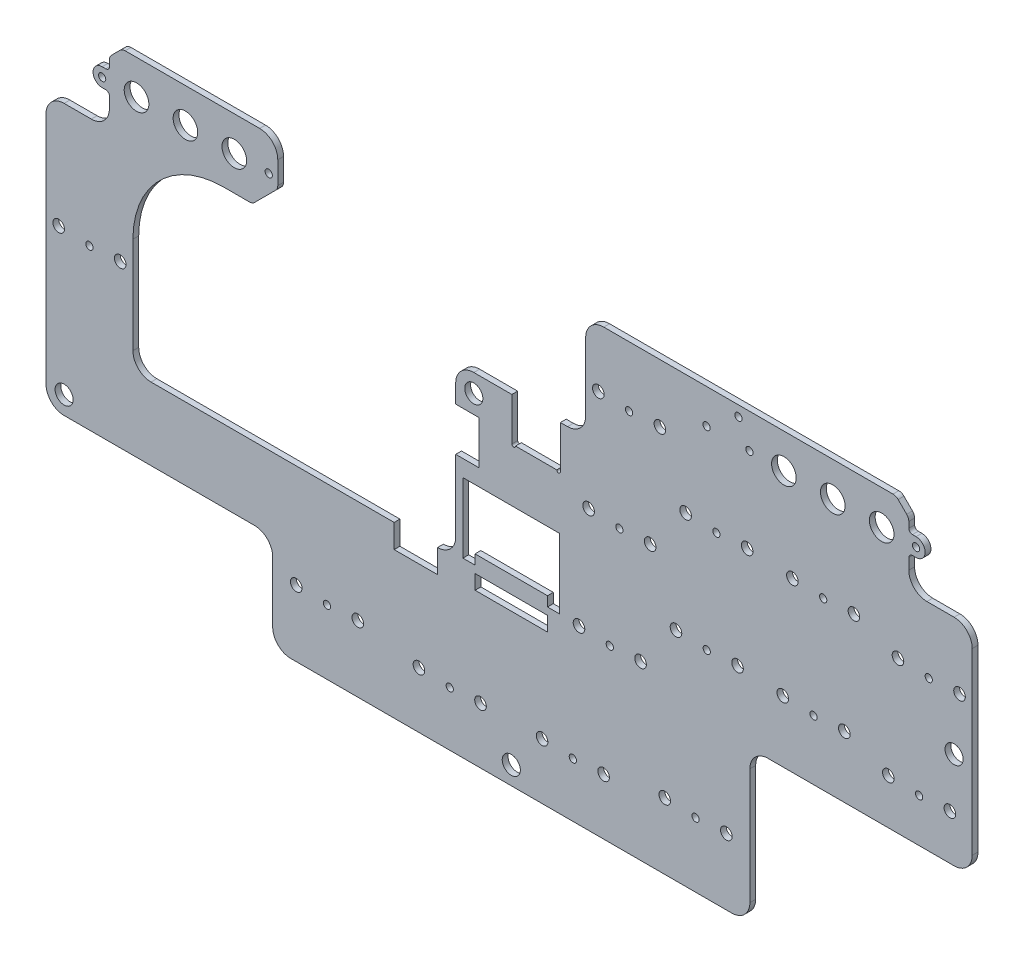
SolidWorks part; units mm, degrees
ref_plane "Front Plane" through (0, 0, 0) normal (0, 0, 1) x (1, 0, 0)
ref_plane "Top Plane" through (0, 0, 0) normal (0, 1, 0) x (1, 0, 0)
ref_plane "Right Plane" through (0, 0, 0) normal (1, 0, 0) x (0, 0, -1)
sketch "Sketch1" plane through (0, 0, 0) normal (0, 0, 1) x (1, 0, 0)
  line L0 (157.8919, 26.2701) -> (191.7747, 29.0915)
  line L1 (157.8919, 26.2701) -> (191.7747, 26.2701)
  line L2 (157.8919, 26.2701) -> (157.8919, 29.0915)
  line L3 (157.8919, 29.0915) -> (191.7747, 29.0915)
  line L4 (191.7747, 26.2701) -> (191.7747, 29.0915)
  line L5 (123.8919, 26.2701) -> (90.0092, 26.2701)
  line L6 (123.8919, 26.2701) -> (123.8919, 29.0915)
  line L7 (123.8919, 29.0915) -> (90.0092, 29.0915)
  line L8 (90.0092, 26.2701) -> (90.0092, 29.0915)
  line L9 (90.0092, 29.0915) -> (123.8919, 26.2701)
  line L10 (168.0919, 58.3601) -> (194.8735, 70.7292)
  line L11 (168.0919, 58.3601) -> (194.8735, 58.3601)
  line L12 (168.0919, 58.3601) -> (168.0919, 70.7292)
  line L13 (168.0919, 70.7292) -> (194.8735, 70.7292)
  line L14 (194.8735, 58.3601) -> (194.8735, 70.7292)
  line L15 (194.8735, 70.7292) -> (224.3587, 70.7292)
  line L16 (194.8735, 70.7292) -> (194.8735, 69.7923)
  line L17 (194.8735, 69.7923) -> (224.3587, 69.7923)
  line L18 (224.3587, 70.7292) -> (224.3587, 69.7923)
  line L19 (224.3587, 69.7923) -> (253.5106, 69.7923)
  line L20 (224.3587, 69.7923) -> (224.3587, 65.2742)
  line L21 (224.3587, 65.2742) -> (253.5106, 65.2742)
  line L22 (253.5106, 69.7923) -> (253.5106, 65.2742)
  line L23 (224.3587, 69.7923) -> (194.8735, 70.7292)
  line L24 (253.5106, 65.2742) -> (224.3587, 69.7923)
  line L25 (170.7502, 87.7401) -> (168.0919, 58.3601)
  line L26 (168.0919, 58.3601) -> (170.7502, 58.3601)
  line L27 (168.0919, 58.3601) -> (168.0919, 87.7401)
  line L28 (168.0919, 87.7401) -> (170.7502, 87.7401)
  line L29 (170.7502, 58.3601) -> (170.7502, 87.7401)
  line L30 (52.9966, 89.4705) -> (24.4119, 82.1791)
  line L31 (24.4119, 82.1791) -> (52.9966, 82.1791)
  line L32 (24.4119, 82.1791) -> (24.4119, 89.4705)
  line L33 (24.4119, 89.4705) -> (52.9966, 89.4705)
  line L34 (52.9966, 82.1791) -> (52.9966, 89.4705)
  line L35 (82.4966, 89.4705) -> (109.0019, 89.4705)
  line L36 (82.4966, 89.4705) -> (82.4966, 76.5201)
  line L37 (82.4966, 76.5201) -> (109.0019, 76.5201)
  line L38 (109.0019, 89.4705) -> (109.0019, 76.5201)
  line L39 (92.4554, 117.2387) -> (82.4966, 117.2387)
  line L40 (92.4554, 117.2387) -> (92.4554, 89.4705)
  line L41 (92.4554, 89.4705) -> (82.4966, 89.4705)
  line L42 (82.4966, 117.2387) -> (82.4966, 89.4705)
  line L43 (92.4554, 117.2387) -> (82.4966, 89.4705)
  line L44 (109.0019, 76.5201) -> (82.4966, 89.4705)
  circle A0 centre (123.8919, 26.2701) radius 14.25
  circle A1 centre (157.8919, 26.2701) radius 14.25
  circle A2 centre (90.0092, 29.0915) radius 14.25
  circle A3 centre (191.7747, 29.0915) radius 14.25
  circle A4 centre (82.4966, 89.4705) radius 11.25
  circle A5 centre (92.4554, 117.2387) radius 11.25
  circle A6 centre (52.9966, 89.4705) radius 11.25
  circle A7 centre (109.0019, 76.5201) radius 11.25
  circle A8 centre (24.4119, 82.1791) radius 11.25
  circle A9 centre (170.7502, 87.7401) radius 11.25
  circle A10 centre (168.0919, 58.3601) radius 11.25
  circle A11 centre (197.5318, 100.1092) radius 11.25
  circle A12 centre (194.8735, 70.7292) radius 11.25
  circle A13 centre (227.0169, 99.1723) radius 11.25
  circle A14 centre (224.3587, 69.7923) radius 11.25
  circle A15 centre (256.1689, 94.6541) radius 11.25
  circle A16 centre (253.5106, 65.2742) radius 11.25
  circle A17 centre (24.4119, 82.1791) radius 12
  circle A18 centre (52.9966, 89.4705) radius 12
  circle A19 centre (92.4554, 117.2387) radius 12
  circle A20 centre (82.4966, 89.4705) radius 12
  circle A21 centre (109.0019, 76.5201) radius 12
  circle A22 centre (168.0919, 58.3601) radius 12
  circle A23 centre (194.8735, 70.7292) radius 12
  circle A24 centre (224.3587, 69.7923) radius 12
  circle A25 centre (253.5106, 65.2742) radius 12
  circle A26 centre (256.1689, 94.6541) radius 12
  circle A27 centre (227.0169, 99.1723) radius 12
  circle A28 centre (197.5318, 100.1092) radius 12
  circle A29 centre (170.7502, 87.7401) radius 12
  circle A30 centre (191.7747, 29.0915) radius 15
  circle A31 centre (157.8919, 26.2701) radius 15
  circle A32 centre (123.8919, 26.2701) radius 15
  circle A33 centre (90.0092, 29.0915) radius 15
  circle A34 centre (173.429, 117.1182) radius 11.25
  circle A35 centre (173.429, 117.1182) radius 12
  dimension "D1" = 28.5
  dimension "D2" = 22.5
  dimension "D3" = 0.75
  dimension "D4" = 0.75
  dimension "D34" = 34
  dimension "D5" = 29.5
  dimension "D6" = 29.5
  dimension "D7" = 29.5
  dimension "D8" = 29.5
  dimension "D9" = 29.5
  dimension "D10" = 29.5
  dimension "D11" = 29.5
  dimension "D12" = 29.5
  dimension "D13" = 29.5
  dimension "D14" = 29.5
  dimension "D15" = 29.5
  dimension "D16" = 29.5
  dimension "D17" = 29.5
  dimension "D18" = 29.5
  dimension "D19" = 34
  dimension "D20" = 34
  dimension "D21" = 32.09
  dimension "D22" = 10.2
  dimension "D23" = 4.76
  dimension "D24" = 4.76
  dimension "D25" = 24.79
  dimension "D26" = 1.82
  dimension "D27" = 8.81
  dimension "D28" = 84.83
  dimension "D29" = 75.69
  dimension "D30" = 70.27
  dimension "D31" = 26.04
  dimension "D32" = 14.89
  dimension "D33" = 50.25
  dimension "D35" = 29.5
  dimension "D36" = 29.5
sketch "Sketch4" plane through (-30.2083, 20.075, 0) normal (0, 0, 1) x (0.9781, -0.2079, 0)
  line L0 (86.1706, 94.1917) -> (105.2206, 75.1417)
  line L1 (67.1206, 94.1917) -> (86.1706, 94.1917)
  line L2 (67.1206, 94.1917) -> (67.1206, 75.1417)
  line L3 (67.1206, 75.1417) -> (86.1706, 75.1417)
  line L4 (86.1706, 94.1917) -> (86.1706, 75.1417)
  line L5 (86.1706, 94.1917) -> (105.2206, 94.1917)
  line L6 (86.1706, 94.1917) -> (86.1706, 75.1417)
  line L7 (86.1706, 75.1417) -> (105.2206, 75.1417)
  line L8 (105.2206, 94.1917) -> (105.2206, 75.1417)
  line L9 (105.2206, 94.1917) -> (124.2706, 94.1917)
  line L10 (105.2206, 94.1917) -> (105.2206, 75.1417)
  line L11 (105.2206, 75.1417) -> (124.2706, 75.1417)
  line L12 (124.2706, 94.1917) -> (124.2706, 75.1417)
  line L13 (86.1706, 94.1917) -> (105.2206, 94.1917)
  line L14 (86.1706, 94.1917) -> (86.1706, 113.2417)
  line L15 (86.1706, 113.2417) -> (105.2206, 113.2417)
  line L16 (105.2206, 94.1917) -> (105.2206, 113.2417)
  line L17 (66.9585, 85.1784) -> (124.4326, 84.1551)
  point P14 (95.6956, 84.6667)
  point P15 (95.6956, 84.6667)
  dimension "D1" = 19.05
sketch "Sketch9" plane through (0, 0, 0) normal (0, 0, 1) x (1, 0, 0)
  line L1 (17.3619, 89.2291) -> (31.4619, 89.2291)
  line L2 (17.3619, 89.2291) -> (17.3619, 75.1291)
  line L3 (17.3619, 75.1291) -> (31.4619, 75.1291)
  line L4 (31.4619, 89.2291) -> (31.4619, 75.1291)
  line L5 (45.9466, 96.5205) -> (60.0466, 96.5205)
  line L6 (45.9466, 96.5205) -> (45.9466, 82.4205)
  line L7 (45.9466, 82.4205) -> (60.0466, 82.4205)
  line L8 (60.0466, 96.5205) -> (60.0466, 82.4205)
  line L9 (75.4466, 96.5205) -> (89.5466, 96.5205)
  line L10 (75.4466, 96.5205) -> (75.4466, 82.4205)
  line L11 (75.4466, 82.4205) -> (89.5466, 82.4205)
  line L12 (89.5466, 96.5205) -> (89.5466, 82.4205)
  line L13 (101.9519, 83.5701) -> (116.0519, 83.5701)
  line L14 (101.9519, 83.5701) -> (101.9519, 69.4701)
  line L15 (101.9519, 69.4701) -> (116.0519, 69.4701)
  line L16 (116.0519, 83.5701) -> (116.0519, 69.4701)
  line L17 (85.4054, 124.2887) -> (99.5054, 124.2887)
  line L18 (85.4054, 124.2887) -> (85.4054, 110.1887)
  line L19 (85.4054, 110.1887) -> (99.5054, 110.1887)
  line L20 (99.5054, 124.2887) -> (99.5054, 110.1887)
  line L21 (82.9592, 36.1415) -> (97.0592, 36.1415)
  line L22 (82.9592, 36.1415) -> (82.9592, 22.0415)
  line L23 (82.9592, 22.0415) -> (97.0592, 22.0415)
  line L24 (97.0592, 36.1415) -> (97.0592, 22.0415)
  line L25 (116.8419, 33.3201) -> (130.9419, 33.3201)
  line L26 (116.8419, 33.3201) -> (116.8419, 19.2201)
  line L27 (116.8419, 19.2201) -> (130.9419, 19.2201)
  line L28 (130.9419, 33.3201) -> (130.9419, 19.2201)
  line L29 (150.8419, 33.3201) -> (164.9419, 33.3201)
  line L30 (150.8419, 33.3201) -> (150.8419, 19.2201)
  line L31 (150.8419, 19.2201) -> (164.9419, 19.2201)
  line L32 (164.9419, 33.3201) -> (164.9419, 19.2201)
  line L33 (184.7247, 36.1415) -> (198.8247, 36.1415)
  line L34 (184.7247, 36.1415) -> (184.7247, 22.0415)
  line L35 (184.7247, 22.0415) -> (198.8247, 22.0415)
  line L36 (198.8247, 36.1415) -> (198.8247, 22.0415)
  line L37 (260.5606, 58.2242) -> (246.4606, 58.2242)
  line L38 (260.5606, 58.2242) -> (260.5606, 72.3242)
  line L39 (260.5606, 72.3242) -> (246.4606, 72.3242)
  line L40 (246.4606, 58.2242) -> (246.4606, 72.3242)
  line L41 (217.3087, 76.8423) -> (231.4087, 76.8423)
  line L42 (217.3087, 76.8423) -> (217.3087, 62.7423)
  line L43 (217.3087, 62.7423) -> (231.4087, 62.7423)
  line L44 (231.4087, 76.8423) -> (231.4087, 62.7423)
  line L45 (187.8235, 77.7792) -> (201.9235, 77.7792)
  line L46 (187.8235, 77.7792) -> (187.8235, 63.6792)
  line L47 (187.8235, 63.6792) -> (201.9235, 63.6792)
  line L48 (201.9235, 77.7792) -> (201.9235, 63.6792)
  line L49 (161.0419, 65.4101) -> (175.1419, 65.4101)
  line L50 (161.0419, 65.4101) -> (161.0419, 51.3101)
  line L51 (161.0419, 51.3101) -> (175.1419, 51.3101)
  line L52 (175.1419, 65.4101) -> (175.1419, 51.3101)
  line L53 (163.7002, 94.7901) -> (177.8002, 94.7901)
  line L54 (163.7002, 94.7901) -> (163.7002, 80.6901)
  line L55 (163.7002, 80.6901) -> (177.8002, 80.6901)
  line L56 (177.8002, 94.7901) -> (177.8002, 80.6901)
  line L57 (190.4818, 107.1592) -> (204.5818, 107.1592)
  line L58 (190.4818, 107.1592) -> (190.4818, 93.0592)
  line L59 (190.4818, 93.0592) -> (204.5818, 93.0592)
  line L60 (204.5818, 107.1592) -> (204.5818, 93.0592)
  line L61 (219.9669, 106.2223) -> (234.0669, 106.2223)
  line L62 (219.9669, 106.2223) -> (219.9669, 92.1223)
  line L63 (219.9669, 92.1223) -> (234.0669, 92.1223)
  line L64 (234.0669, 106.2223) -> (234.0669, 92.1223)
  line L65 (249.1189, 101.7041) -> (263.2189, 101.7041)
  line L66 (249.1189, 101.7041) -> (249.1189, 87.6041)
  line L67 (249.1189, 87.6041) -> (263.2189, 87.6041)
  line L68 (263.2189, 101.7041) -> (263.2189, 87.6041)
  line L69 (166.379, 124.1682) -> (180.479, 124.1682)
  line L70 (166.379, 124.1682) -> (166.379, 110.0682)
  line L71 (166.379, 110.0682) -> (180.479, 110.0682)
  line L72 (180.479, 124.1682) -> (180.479, 110.0682)
  point P72 (24.4119, 89.2291)
  point P74 (52.9966, 96.5205)
  point P76 (82.4966, 96.5205)
  point P78 (92.4554, 124.2887)
  point P80 (109.0019, 83.5701)
  point P82 (90.0092, 36.1415)
  point P84 (123.8919, 33.3201)
  point P86 (157.8919, 33.3201)
  point P88 (191.7747, 36.1415)
  point P90 (168.0919, 65.4101)
  point P92 (170.7502, 94.7901)
  point P94 (173.429, 124.1682)
  point P96 (197.5318, 107.1592)
  point P98 (227.0169, 106.2223)
  point P100 (256.1689, 101.7041)
  point P102 (194.8735, 77.7792)
  point P104 (224.3587, 76.8423)
  point P106 (253.5106, 72.3242)
  point P108 (17.3619, 82.1791)
  point P109 (45.9466, 89.4705)
  point P110 (75.4466, 89.4705)
  point P111 (101.9519, 76.5201)
  point P112 (85.4054, 117.2387)
  point P113 (82.9592, 29.0915)
  point P114 (116.8419, 26.2701)
  point P115 (150.8419, 26.2701)
  point P116 (184.7247, 29.0915)
  point P118 (161.0419, 58.3601)
  point P119 (187.8235, 70.7292)
  point P120 (217.3087, 69.7923)
  point P121 (246.4606, 65.2742)
  point P122 (163.7002, 87.7401)
  point P123 (190.4818, 100.1092)
  point P124 (219.9669, 99.1723)
  point P125 (249.1189, 94.6541)
  point P126 (166.379, 117.1182)
  dimension "D1" = 14.1
sketch "Sketch10" plane through (-22.0981, 19.3454, 0) normal (0, 0, 1) x (0.9781, -0.2079, 0)
  line L1 (61.5108, 90.7441) -> (75.6108, 90.7441)
  line L2 (61.5108, 90.7441) -> (61.5108, 76.6441)
  line L3 (61.5108, 76.6441) -> (75.6108, 76.6441)
  line L4 (75.6108, 90.7441) -> (75.6108, 76.6441)
  line L5 (80.5608, 90.7441) -> (94.6608, 90.7441)
  line L6 (80.5608, 90.7441) -> (80.5608, 76.6441)
  line L7 (80.5608, 76.6441) -> (94.6608, 76.6441)
  line L8 (94.6608, 90.7441) -> (94.6608, 76.6441)
  line L9 (99.6108, 90.7441) -> (113.7108, 90.7441)
  line L10 (99.6108, 90.7441) -> (99.6108, 76.6441)
  line L11 (99.6108, 76.6441) -> (113.7108, 76.6441)
  line L12 (113.7108, 90.7441) -> (113.7108, 76.6441)
  line L13 (80.5608, 109.7941) -> (94.6608, 109.7941)
  line L14 (80.5608, 109.7941) -> (80.5608, 95.6941)
  line L15 (80.5608, 95.6941) -> (94.6608, 95.6941)
  line L16 (94.6608, 109.7941) -> (94.6608, 95.6941)
  line L17 (50.5121, 89.6359) -> (53.4436, 75.8441) construction
  line L18 (59.0358, 93.2191) -> (78.0858, 93.2191) construction
  line L19 (78.0858, 112.2691) -> (97.1358, 112.2691) construction
  line L20 (97.1358, 93.2191) -> (116.1858, 93.2191) construction
  line L21 (78.0858, 93.2191) -> (78.0858, 112.2691) construction
  line L23 (59.0358, 93.2191) -> (59.0358, 74.1691) construction
  point P16 (75.6108, 83.6941)
  point P17 (94.6608, 83.6941)
  point P18 (113.7108, 83.6941)
  point P19 (87.6108, 90.7441)
  point P20 (87.6108, 109.7941)
  point P23 (68.5608, 90.7441)
  point P26 (68.5608, 93.2191)
  point P29 (87.6108, 112.2691)
  point P30 (106.6608, 90.7441)
  point P33 (106.6608, 93.2191)
  point P34 (80.5608, 102.7441)
  point P37 (78.0858, 102.7441)
  point P42 (59.0358, 83.6941)
  point P43 (61.5108, 83.6941)
sketch "Sketch14" plane through (0, 0, 0) normal (0, 0, 1) x (1, 0, 0)
  line L0 (165.1144, 80.6901) -> (163.7002, 82.1043)
  line L1 (163.7002, 93.3758) -> (165.1144, 94.7901)
  line L2 (177.8002, 93.3758) -> (176.386, 94.7901)
  line L3 (179.0648, 110.0682) -> (180.479, 111.4824)
  line L4 (166.379, 111.4824) -> (167.7932, 110.0682)
  line L5 (166.379, 122.754) -> (167.7932, 124.1682)
  line L6 (179.0648, 124.1682) -> (180.479, 122.754)
  line L7 (203.1676, 93.0592) -> (204.5818, 94.4734)
  line L8 (17.3619, 89.2291) -> (17.3619, 75.1291) construction
  line L9 (17.3619, 89.2291) -> (31.4619, 89.2291) construction
  line L10 (17.3619, 87.8149) -> (18.7761, 89.2291)
  line L11 (17.3619, 75.1291) -> (31.4619, 75.1291) construction
  line L12 (31.4619, 89.2291) -> (31.4619, 75.1291) construction
  line L13 (45.9466, 96.5205) -> (60.0466, 96.5205) construction
  line L14 (60.0466, 96.5205) -> (60.0466, 82.4205) construction
  line L15 (45.9466, 96.5205) -> (45.9466, 82.4205) construction
  line L16 (45.9466, 82.4205) -> (60.0466, 82.4205) construction
  line L17 (85.4054, 124.2887) -> (85.4054, 110.1887) construction
  line L18 (85.4054, 124.2887) -> (99.5054, 124.2887) construction
  line L19 (99.5054, 124.2887) -> (99.5054, 110.1887) construction
  line L20 (85.4054, 110.1887) -> (99.5054, 110.1887) construction
  line L21 (101.9519, 83.5701) -> (101.9519, 69.4701) construction
  line L22 (101.9519, 83.5701) -> (116.0519, 83.5701) construction
  line L23 (116.0519, 83.5701) -> (116.0519, 69.4701) construction
  line L24 (101.9519, 69.4701) -> (116.0519, 69.4701) construction
  line L25 (91.2712, 73.6044) -> (105.0631, 70.6729) construction
  line L26 (107.9947, 84.4647) -> (105.0631, 70.6729) construction
  line L27 (94.2028, 87.3963) -> (107.9947, 84.4647) construction
  line L28 (94.2028, 87.3963) -> (91.2712, 73.6044) construction
  line L29 (72.6375, 77.5651) -> (86.4294, 74.6336) construction
  line L30 (89.361, 88.4255) -> (86.4294, 74.6336) construction
  line L31 (75.5691, 91.357) -> (89.361, 88.4255) construction
  line L32 (75.5691, 91.357) -> (72.6375, 77.5651) construction
  line L33 (56.9354, 95.3177) -> (54.0038, 81.5259) construction
  line L34 (56.9354, 95.3177) -> (70.7273, 92.3862) construction
  line L35 (70.7273, 92.3862) -> (67.7957, 78.5943) construction
  line L36 (54.0038, 81.5259) -> (67.7957, 78.5943) construction
  line L37 (76.5983, 96.1988) -> (90.3901, 93.2673) construction
  line L38 (93.3217, 107.0592) -> (90.3901, 93.2673) construction
  line L39 (79.5298, 109.9907) -> (76.5983, 96.1988) construction
  line L40 (79.5298, 109.9907) -> (93.3217, 107.0592) construction
  line L41 (82.9592, 36.1415) -> (82.9592, 22.0415) construction
  line L42 (82.9592, 36.1415) -> (97.0592, 36.1415) construction
  line L43 (82.9592, 22.0415) -> (97.0592, 22.0415) construction
  line L44 (97.0592, 36.1415) -> (97.0592, 22.0415) construction
  line L45 (116.8419, 33.3201) -> (116.8419, 19.2201) construction
  line L46 (116.8419, 33.3201) -> (130.9419, 33.3201) construction
  line L47 (116.8419, 19.2201) -> (130.9419, 19.2201) construction
  line L48 (130.9419, 33.3201) -> (130.9419, 19.2201) construction
  line L49 (150.8419, 33.3201) -> (150.8419, 19.2201) construction
  line L50 (150.8419, 33.3201) -> (164.9419, 33.3201) construction
  line L51 (164.9419, 33.3201) -> (164.9419, 19.2201) construction
  line L52 (150.8419, 19.2201) -> (164.9419, 19.2201) construction
  line L53 (184.7247, 36.1415) -> (184.7247, 22.0415) construction
  line L54 (184.7247, 22.0415) -> (198.8247, 22.0415) construction
  line L55 (198.8247, 36.1415) -> (198.8247, 22.0415) construction
  line L56 (184.7247, 36.1415) -> (198.8247, 36.1415) construction
  line L57 (161.0419, 65.4101) -> (175.1419, 65.4101) construction
  line L58 (175.1419, 65.4101) -> (175.1419, 51.3101) construction
  line L59 (161.0419, 51.3101) -> (175.1419, 51.3101) construction
  line L60 (161.0419, 65.4101) -> (161.0419, 51.3101) construction
  line L61 (187.8235, 77.7792) -> (187.8235, 63.6792) construction
  line L62 (187.8235, 77.7792) -> (201.9235, 77.7792) construction
  line L63 (187.8235, 63.6792) -> (201.9235, 63.6792) construction
  line L64 (201.9235, 77.7792) -> (201.9235, 63.6792) construction
  line L65 (217.3087, 76.8423) -> (217.3087, 62.7423) construction
  line L66 (217.3087, 76.8423) -> (231.4087, 76.8423) construction
  line L67 (231.4087, 76.8423) -> (231.4087, 62.7423) construction
  line L68 (217.3087, 62.7423) -> (231.4087, 62.7423) construction
  line L69 (260.5606, 58.2242) -> (246.4606, 58.2242) construction
  line L70 (260.5606, 58.2242) -> (260.5606, 72.3242) construction
  line L71 (246.4606, 58.2242) -> (246.4606, 72.3242) construction
  line L72 (260.5606, 72.3242) -> (246.4606, 72.3242) construction
  line L73 (249.1189, 101.7041) -> (263.2189, 101.7041) construction
  line L74 (263.2189, 101.7041) -> (263.2189, 87.6041) construction
  line L75 (249.1189, 87.6041) -> (263.2189, 87.6041) construction
  line L76 (249.1189, 101.7041) -> (249.1189, 87.6041) construction
  line L77 (219.9669, 106.2223) -> (219.9669, 92.1223) construction
  line L78 (219.9669, 106.2223) -> (234.0669, 106.2223) construction
  line L79 (234.0669, 106.2223) -> (234.0669, 92.1223) construction
  line L80 (219.9669, 92.1223) -> (234.0669, 92.1223) construction
  line L81 (190.4818, 107.1592) -> (204.5818, 107.1592) construction
  line L82 (204.5818, 107.1592) -> (204.5818, 93.0592) construction
  line L83 (190.4818, 93.0592) -> (204.5818, 93.0592) construction
  line L84 (190.4818, 107.1592) -> (190.4818, 93.0592) construction
  line L85 (163.7002, 94.7901) -> (177.8002, 94.7901) construction
  line L86 (177.8002, 94.7901) -> (177.8002, 80.6901) construction
  line L87 (163.7002, 80.6901) -> (177.8002, 80.6901) construction
  line L88 (163.7002, 94.7901) -> (163.7002, 80.6901) construction
  line L89 (180.479, 124.1682) -> (180.479, 110.0682) construction
  line L90 (166.379, 110.0682) -> (180.479, 110.0682) construction
  line L91 (166.379, 124.1682) -> (166.379, 110.0682) construction
  line L92 (166.379, 124.1682) -> (180.479, 124.1682) construction
  line L93 (17.3619, 76.5433) -> (18.7761, 75.1291)
  line L94 (30.0477, 75.1291) -> (31.4619, 76.5433)
  line L95 (31.4619, 87.8149) -> (30.0477, 89.2291)
  line L96 (45.9466, 95.1063) -> (47.3608, 96.5205)
  line L97 (45.9466, 83.8347) -> (47.3608, 82.4205)
  line L98 (54.2979, 82.9092) -> (55.3871, 81.2318)
  line L99 (58.6323, 82.4205) -> (60.0466, 83.8347)
  line L100 (56.6413, 93.9344) -> (58.3187, 95.0237)
  line L101 (58.6323, 96.5205) -> (60.0466, 95.1063)
  line L102 (69.3439, 92.6802) -> (70.4332, 91.0029)
  line L103 (68.0897, 79.9776) -> (66.4124, 78.8883)
  line L104 (75.2751, 89.9737) -> (76.9524, 91.063)
  line L105 (72.9316, 78.9484) -> (74.0208, 77.2711)
  line L106 (85.0461, 74.9276) -> (86.7234, 76.0169)
  line L107 (89.0669, 87.0421) -> (87.9777, 88.7195)
  line L108 (89.0068, 93.5613) -> (90.6842, 94.6506)
  line L109 (76.8923, 97.5822) -> (77.9816, 95.9048)
  line L110 (91.9384, 107.3532) -> (93.0277, 105.6759)
  line L111 (79.2358, 108.6074) -> (80.9131, 109.6967)
  line L112 (85.4054, 111.6029) -> (86.8196, 110.1887)
  line L113 (98.0912, 110.1887) -> (99.5054, 111.6029)
  line L114 (98.0912, 124.2887) -> (99.5054, 122.8745)
  line L115 (85.4054, 122.8745) -> (86.8196, 124.2887)
  line L116 (93.9088, 86.013) -> (95.5861, 87.1023)
  line L117 (91.5653, 74.9877) -> (92.6546, 73.3104)
  line L118 (103.6798, 70.9669) -> (105.3572, 72.0562)
  line L119 (106.6114, 84.7588) -> (107.7006, 83.0814)
  line L120 (101.9519, 82.1559) -> (103.3662, 83.5701)
  line L121 (101.9519, 70.8843) -> (103.3662, 69.4701)
  line L122 (114.6377, 69.4701) -> (116.0519, 70.8843)
  line L123 (116.0519, 82.1559) -> (114.6377, 83.5701)
  line L124 (82.9592, 34.7272) -> (84.3734, 36.1415)
  line L125 (82.9592, 23.4557) -> (84.3734, 22.0415)
  line L126 (95.645, 22.0415) -> (97.0592, 23.4557)
  line L127 (97.0592, 34.7272) -> (95.645, 36.1415)
  line L128 (116.8419, 31.9059) -> (118.2562, 33.3201)
  line L129 (116.8419, 20.6343) -> (118.2562, 19.2201)
  line L130 (129.5277, 19.2201) -> (130.9419, 20.6343)
  line L131 (130.9419, 31.9059) -> (129.5277, 33.3201)
  line L132 (150.8419, 31.9059) -> (152.2562, 33.3201)
  line L133 (150.8419, 20.6343) -> (152.2562, 19.2201)
  line L134 (163.5277, 19.2201) -> (164.9419, 20.6343)
  line L135 (164.9419, 31.9059) -> (163.5277, 33.3201)
  line L136 (184.7247, 34.7272) -> (186.1389, 36.1415)
  line L137 (184.7247, 23.4557) -> (186.1389, 22.0415)
  line L138 (197.4105, 22.0415) -> (198.8247, 23.4557)
  line L139 (198.8247, 34.7272) -> (197.4105, 36.1415)
  line L140 (173.7277, 51.3101) -> (175.1419, 52.7243)
  line L141 (161.0419, 52.7243) -> (162.4562, 51.3101)
  line L142 (161.0419, 63.9959) -> (162.4562, 65.4101)
  line L143 (173.7277, 65.4101) -> (175.1419, 63.9959)
  line L144 (187.8235, 65.0934) -> (189.2378, 63.6792)
  line L145 (200.5093, 63.6792) -> (201.9235, 65.0934)
  line L146 (200.5093, 77.7792) -> (201.9235, 76.365)
  line L147 (187.8235, 76.365) -> (189.2378, 77.7792)
  line L148 (176.386, 80.6901) -> (177.8002, 82.1043)
  line L149 (204.5818, 105.745) -> (203.1676, 107.1592)
  line L150 (191.896, 107.1592) -> (190.4818, 105.745)
  line L151 (190.4818, 94.4734) -> (191.896, 93.0592)
  line L152 (219.9669, 104.8081) -> (221.3812, 106.2223)
  line L153 (232.6527, 106.2223) -> (234.0669, 104.8081)
  line L154 (234.0669, 93.5365) -> (232.6527, 92.1223)
  line L155 (219.9669, 93.5365) -> (221.3812, 92.1223)
  line L156 (229.9944, 76.8423) -> (231.4087, 75.4281)
  line L157 (217.3087, 75.4281) -> (218.7229, 76.8423)
  line L158 (217.3087, 64.1565) -> (218.7229, 62.7423)
  line L159 (229.9944, 62.7423) -> (231.4087, 64.1565)
  line L160 (259.1464, 72.3242) -> (260.5606, 70.9099)
  line L161 (246.4606, 70.9099) -> (247.8748, 72.3242)
  line L162 (259.1464, 58.2242) -> (260.5606, 59.6384)
  line L163 (247.8748, 58.2242) -> (246.4606, 59.6384)
  line L164 (261.8047, 87.6041) -> (263.2189, 89.0183)
  line L165 (249.1189, 89.0183) -> (250.5331, 87.6041)
  line L166 (249.1189, 100.2899) -> (250.5331, 101.7041)
  line L167 (261.8047, 101.7041) -> (263.2189, 100.2899)
  line L168 (75.4466, 96.5205) -> (75.4466, 82.4205) construction
  line L169 (75.4466, 96.5205) -> (89.5466, 96.5205) construction
  line L170 (89.5466, 96.5205) -> (89.5466, 82.4205) construction
  line L171 (75.4466, 82.4205) -> (89.5466, 82.4205) construction
  line L172 (76.8608, 96.5205) -> (75.4466, 95.1063)
  line L173 (88.1323, 96.5205) -> (89.5466, 95.1063)
  line L174 (89.5466, 83.8347) -> (88.1323, 82.4205)
  line L175 (75.4466, 83.8347) -> (76.8608, 82.4205)
  arc A0 (17.3619, 87.8149) -> (18.7761, 89.2291) centre (18.069, 88.522) cw
  arc A1 (18.7761, 75.1291) -> (17.3619, 76.5433) centre (18.069, 75.8362) cw
  arc A2 (31.4619, 76.5433) -> (30.0477, 75.1291) centre (30.7548, 75.8362) cw
  arc A3 (30.0477, 89.2291) -> (31.4619, 87.8149) centre (30.7548, 88.522) cw
  arc A4 (58.6323, 96.5205) -> (60.0466, 95.1063) centre (59.3394, 95.8134) cw
  arc A5 (45.9466, 95.1063) -> (47.3608, 96.5205) centre (46.6537, 95.8134) cw
  arc A6 (47.3608, 82.4205) -> (45.9466, 83.8347) centre (46.6537, 83.1276) cw
  arc A7 (60.0466, 83.8347) -> (58.6323, 82.4205) centre (59.3394, 83.1276) cw
  arc A8 (85.4054, 122.8745) -> (86.8196, 124.2887) centre (86.1125, 123.5816) cw
  arc A9 (98.0912, 124.2887) -> (99.5054, 122.8745) centre (98.7983, 123.5816) cw
  arc A10 (99.5054, 111.6029) -> (98.0912, 110.1887) centre (98.7983, 110.8958) cw
  arc A11 (85.4054, 111.6029) -> (86.8196, 110.1887) centre (86.1125, 110.8958) ccw
  arc A12 (101.9519, 82.1559) -> (103.3662, 83.5701) centre (102.6591, 82.863) cw
  arc A13 (114.6377, 83.5701) -> (116.0519, 82.1559) centre (115.3448, 82.863) cw
  arc A14 (116.0519, 70.8843) -> (114.6377, 69.4701) centre (115.3448, 70.1772) cw
  arc A15 (101.9519, 70.8843) -> (103.3662, 69.4701) centre (102.6591, 70.1772) ccw
  arc A16 (103.6798, 70.9669) -> (105.3572, 72.0562) centre (104.5185, 71.5115) ccw
  arc A17 (106.6114, 84.7588) -> (107.7006, 83.0814) centre (107.156, 83.9201) cw
  arc A18 (93.9088, 86.013) -> (95.5861, 87.1023) centre (94.7474, 86.5576) cw
  arc A19 (91.5653, 74.9877) -> (92.6546, 73.3104) centre (92.1099, 74.1491) ccw
  arc A20 (85.0461, 74.9276) -> (86.7234, 76.0169) centre (85.8848, 75.4722) ccw
  arc A21 (87.9777, 88.7195) -> (89.0669, 87.0421) centre (88.5223, 87.8808) cw
  arc A22 (75.2751, 89.9737) -> (76.9524, 91.063) centre (76.1137, 90.5183) cw
  arc A23 (72.9316, 78.9484) -> (74.0208, 77.2711) centre (73.4762, 78.1098) ccw
  arc A24 (56.6413, 93.9344) -> (58.3187, 95.0237) centre (57.48, 94.4791) cw
  arc A25 (69.3439, 92.6802) -> (70.4332, 91.0029) centre (69.8886, 91.8415) cw
  arc A26 (68.0897, 79.9776) -> (66.4124, 78.8883) centre (67.2511, 79.433) cw
  arc A27 (54.2979, 82.9092) -> (55.3871, 81.2318) centre (54.8425, 82.0705) ccw
  arc A28 (89.0068, 93.5613) -> (90.6842, 94.6506) centre (89.8455, 94.106) ccw
  arc A29 (76.8923, 97.5822) -> (77.9816, 95.9048) centre (77.4369, 96.7435) ccw
  arc A30 (79.2358, 108.6074) -> (80.9131, 109.6967) centre (80.0744, 109.1521) cw
  arc A31 (91.9384, 107.3532) -> (93.0277, 105.6759) centre (92.483, 106.5145) cw
  arc A32 (82.9592, 34.7272) -> (84.3734, 36.1415) centre (83.6663, 35.4344) cw
  arc A33 (82.9592, 23.4557) -> (84.3734, 22.0415) centre (83.6663, 22.7486) ccw
  arc A34 (95.645, 22.0415) -> (97.0592, 23.4557) centre (96.3521, 22.7486) ccw
  arc A35 (95.645, 36.1415) -> (97.0592, 34.7272) centre (96.3521, 35.4344) cw
  arc A36 (116.8419, 31.9059) -> (118.2562, 33.3201) centre (117.5491, 32.613) cw
  arc A37 (116.8419, 20.6343) -> (118.2562, 19.2201) centre (117.5491, 19.9272) ccw
  arc A38 (129.5277, 19.2201) -> (130.9419, 20.6343) centre (130.2348, 19.9272) ccw
  arc A39 (129.5277, 33.3201) -> (130.9419, 31.9059) centre (130.2348, 32.613) cw
  arc A40 (150.8419, 31.9059) -> (152.2562, 33.3201) centre (151.5491, 32.613) cw
  arc A41 (163.5277, 33.3201) -> (164.9419, 31.9059) centre (164.2348, 32.613) cw
  arc A42 (164.9419, 20.6343) -> (163.5277, 19.2201) centre (164.2348, 19.9272) cw
  arc A43 (150.8419, 20.6343) -> (152.2562, 19.2201) centre (151.5491, 19.9272) ccw
  arc A44 (184.7247, 23.4557) -> (186.1389, 22.0415) centre (185.4318, 22.7486) ccw
  arc A45 (197.4105, 22.0415) -> (198.8247, 23.4557) centre (198.1176, 22.7486) ccw
  arc A46 (197.4105, 36.1415) -> (198.8247, 34.7272) centre (198.1176, 35.4344) cw
  arc A47 (184.7247, 34.7272) -> (186.1389, 36.1415) centre (185.4318, 35.4344) cw
  arc A48 (173.7277, 65.4101) -> (175.1419, 63.9959) centre (174.4348, 64.703) cw
  arc A49 (175.1419, 52.7243) -> (173.7277, 51.3101) centre (174.4348, 52.0172) cw
  arc A50 (161.0419, 52.7243) -> (162.4562, 51.3101) centre (161.7491, 52.0172) ccw
  arc A51 (161.0419, 63.9959) -> (162.4562, 65.4101) centre (161.7491, 64.703) cw
  arc A52 (187.8235, 76.365) -> (189.2378, 77.7792) centre (188.5306, 77.0721) cw
  arc A53 (187.8235, 65.0934) -> (189.2378, 63.6792) centre (188.5306, 64.3863) ccw
  arc A54 (200.5093, 63.6792) -> (201.9235, 65.0934) centre (201.2164, 64.3863) ccw
  arc A55 (200.5093, 77.7792) -> (201.9235, 76.365) centre (201.2164, 77.0721) cw
  arc A56 (217.3087, 75.4281) -> (218.7229, 76.8423) centre (218.0158, 76.1352) cw
  arc A57 (229.9944, 76.8423) -> (231.4087, 75.4281) centre (230.7016, 76.1352) cw
  arc A58 (231.4087, 64.1565) -> (229.9944, 62.7423) centre (230.7016, 63.4494) cw
  arc A59 (217.3087, 64.1565) -> (218.7229, 62.7423) centre (218.0158, 63.4494) ccw
  arc A60 (259.1464, 58.2242) -> (260.5606, 59.6384) centre (259.8535, 58.9313) ccw
  arc A61 (246.4606, 59.6384) -> (247.8748, 58.2242) centre (247.1677, 58.9313) ccw
  arc A62 (246.4606, 70.9099) -> (247.8748, 72.3242) centre (247.1677, 71.617) cw
  arc A63 (259.1464, 72.3242) -> (260.5606, 70.9099) centre (259.8535, 71.617) cw
  arc A64 (261.8047, 101.7041) -> (263.2189, 100.2899) centre (262.5118, 100.997) cw
  arc A65 (263.2189, 89.0183) -> (261.8047, 87.6041) centre (262.5118, 88.3112) cw
  arc A66 (250.5331, 87.6041) -> (249.1189, 89.0183) centre (249.826, 88.3112) cw
  arc A67 (249.1189, 100.2899) -> (250.5331, 101.7041) centre (249.826, 100.997) cw
  arc A68 (219.9669, 104.8081) -> (221.3812, 106.2223) centre (220.674, 105.5152) cw
  arc A69 (232.6527, 106.2223) -> (234.0669, 104.8081) centre (233.3598, 105.5152) cw
  arc A70 (234.0669, 93.5365) -> (232.6527, 92.1223) centre (233.3598, 92.8294) cw
  arc A71 (221.3812, 92.1223) -> (219.9669, 93.5365) centre (220.674, 92.8294) cw
  arc A72 (203.1676, 107.1592) -> (204.5818, 105.745) centre (203.8747, 106.4521) cw
  arc A73 (204.5818, 94.4734) -> (203.1676, 93.0592) centre (203.8747, 93.7663) cw
  arc A74 (191.896, 93.0592) -> (190.4818, 94.4734) centre (191.1889, 93.7663) cw
  arc A75 (190.4818, 105.745) -> (191.896, 107.1592) centre (191.1889, 106.4521) cw
  arc A76 (176.386, 94.7901) -> (177.8002, 93.3758) centre (177.0931, 94.0829) cw
  arc A77 (177.8002, 82.1043) -> (176.386, 80.6901) centre (177.0931, 81.3972) cw
  arc A78 (165.1144, 80.6901) -> (163.7002, 82.1043) centre (164.4073, 81.3972) cw
  arc A79 (163.7002, 93.3758) -> (165.1144, 94.7901) centre (164.4073, 94.0829) cw
  arc A80 (180.479, 111.4824) -> (179.0648, 110.0682) centre (179.7719, 110.7753) cw
  arc A81 (167.7932, 110.0682) -> (166.379, 111.4824) centre (167.0861, 110.7753) cw
  arc A82 (179.0648, 124.1682) -> (180.479, 122.754) centre (179.7719, 123.4611) cw
  arc A83 (166.379, 122.754) -> (167.7932, 124.1682) centre (167.0861, 123.4611) cw
  arc A84 (75.4466, 95.1063) -> (76.8608, 96.5205) centre (76.1537, 95.8134) cw
  arc A85 (88.1323, 96.5205) -> (89.5466, 95.1063) centre (88.8394, 95.8134) cw
  arc A86 (89.5466, 83.8347) -> (88.1323, 82.4205) centre (88.8394, 83.1276) cw
  arc A87 (76.8608, 82.4205) -> (75.4466, 83.8347) centre (76.1537, 83.1276) cw
  dimension "D1" = 45
  dimension "D2" = 1
  dimension "D71" = 45
  dimension "D3" = 45
  dimension "D4" = 45
  dimension "D5" = 45
  dimension "D6" = 45
  dimension "D7" = 45
  dimension "D8" = 45
  dimension "D9" = 45
  dimension "D10" = 45
  dimension "D11" = 45
  dimension "D12" = 45
  dimension "D13" = 45
  dimension "D14" = 45
  dimension "D15" = 45
  dimension "D16" = 45
  dimension "D17" = 45
  dimension "D18" = 45
  dimension "D19" = 45
  dimension "D20" = 45
  dimension "D21" = 45
  dimension "D22" = 45
  dimension "D23" = 45
  dimension "D24" = 45
  dimension "D25" = 45
  dimension "D26" = 45
  dimension "D27" = 45
  dimension "D28" = 45
  dimension "D29" = 45
  dimension "D30" = 45
  dimension "D31" = 45
  dimension "D32" = 45
  dimension "D33" = 45
  dimension "D34" = 45
  dimension "D35" = 45
  dimension "D36" = 45
  dimension "D37" = 45
  dimension "D38" = 45
  dimension "D39" = 45
  dimension "D40" = 45
  dimension "D41" = 45
  dimension "D42" = 45
  dimension "D43" = 45
  dimension "D44" = 45
  dimension "D45" = 45
  dimension "D46" = 45
  dimension "D47" = 45
  dimension "D48" = 45
  dimension "D49" = 45
  dimension "D50" = 45
  dimension "D51" = 45
  dimension "D52" = 45
  dimension "D53" = 45
  dimension "D54" = 45
  dimension "D55" = 45
  dimension "D56" = 45
  dimension "D57" = 45
  dimension "D58" = 45
  dimension "D59" = 45
  dimension "D60" = 45
  dimension "D61" = 45
  dimension "D62" = 45
  dimension "D63" = 45
  dimension "D64" = 45
  dimension "D65" = 45
  dimension "D66" = 45
  dimension "D67" = 45
  dimension "D68" = 45
  dimension "D69" = 45
  dimension "D70" = 45
  dimension "D72" = 45
  dimension "D73" = 45
  dimension "D74" = 45
  dimension "D75" = 45
  dimension "D76" = 45
  dimension "D77" = 45
  dimension "D78" = 45
  dimension "D79" = 45
  dimension "D80" = 45
  dimension "D81" = 45
  dimension "D82" = 45
  dimension "D83" = 45
  dimension "D84" = 45
  dimension "D85" = 45
  dimension "D86" = 45
  dimension "D87" = 45
  dimension "D88" = 45
  dimension "D89" = 45
sketch "Sketch16" plane through (0, 0, 0) normal (0, 0, 1) x (1, 0, 0)
  line L0 (81.5092, 31.1915) -> (98.5092, 31.1915)
  line L6 (81.5092, 31.1915) -> (81.5092, 27.9915)
  line L7 (17.3619, 75.1291) -> (31.4619, 75.1291) construction
  line L8 (15.9119, 84.2791) -> (32.9119, 84.2791)
  line L9 (15.9119, 84.2791) -> (15.9119, 81.0791)
  line L10 (15.9119, 81.0791) -> (32.9119, 81.0791)
  line L11 (32.9119, 84.2791) -> (32.9119, 81.0791)
  line L12 (81.5092, 27.9915) -> (98.5092, 27.9915)
  line L13 (98.5092, 31.1915) -> (98.5092, 27.9915)
  line L14 (115.3919, 28.3701) -> (132.3919, 28.3701)
  line L15 (115.3919, 28.3701) -> (115.3919, 25.1701)
  line L16 (115.3919, 25.1701) -> (132.3919, 25.1701)
  line L17 (132.3919, 28.3701) -> (132.3919, 25.1701)
  line L18 (149.3919, 28.3701) -> (166.3919, 28.3701)
  line L19 (149.3919, 28.3701) -> (149.3919, 25.1701)
  line L20 (149.3919, 25.1701) -> (166.3919, 25.1701)
  line L21 (166.3919, 28.3701) -> (166.3919, 25.1701)
  line L22 (183.2747, 31.1915) -> (200.2747, 31.1915)
  line L23 (183.2747, 31.1915) -> (183.2747, 27.9915)
  line L24 (183.2747, 27.9915) -> (200.2747, 27.9915)
  line L25 (200.2747, 31.1915) -> (200.2747, 27.9915)
  line L26 (44.4966, 91.5705) -> (61.4966, 91.5705)
  line L27 (44.4966, 91.5705) -> (44.4966, 88.3705)
  line L28 (44.4966, 88.3705) -> (61.4966, 88.3705)
  line L29 (61.4966, 91.5705) -> (61.4966, 88.3705)
  line L30 (73.9966, 91.5705) -> (90.9966, 91.5705)
  line L31 (73.9966, 91.5705) -> (73.9966, 88.3705)
  line L32 (73.9966, 88.3705) -> (90.9966, 88.3705)
  line L33 (90.9966, 91.5705) -> (90.9966, 88.3705)
  line L34 (100.5019, 78.6201) -> (117.5019, 78.6201)
  line L35 (100.5019, 78.6201) -> (100.5019, 75.4201)
  line L36 (100.5019, 75.4201) -> (117.5019, 75.4201)
  line L37 (117.5019, 78.6201) -> (117.5019, 75.4201)
  line L38 (83.9554, 119.3387) -> (100.9554, 119.3387)
  line L39 (83.9554, 119.3387) -> (83.9554, 116.1387)
  line L40 (83.9554, 116.1387) -> (100.9554, 116.1387)
  line L41 (100.9554, 119.3387) -> (100.9554, 116.1387)
  line L42 (164.929, 119.2182) -> (181.929, 119.2182)
  line L43 (164.929, 119.2182) -> (164.929, 116.0182)
  line L44 (164.929, 116.0182) -> (181.929, 116.0182)
  line L45 (181.929, 119.2182) -> (181.929, 116.0182)
  line L46 (162.2502, 89.8401) -> (179.2502, 89.8401)
  line L47 (162.2502, 89.8401) -> (162.2502, 86.6401)
  line L48 (162.2502, 86.6401) -> (179.2502, 86.6401)
  line L49 (179.2502, 89.8401) -> (179.2502, 86.6401)
  line L50 (189.0318, 102.2092) -> (206.0318, 102.2092)
  line L51 (189.0318, 102.2092) -> (189.0318, 99.0092)
  line L52 (189.0318, 99.0092) -> (206.0318, 99.0092)
  line L53 (206.0318, 102.2092) -> (206.0318, 99.0092)
  line L54 (159.5919, 60.4601) -> (176.5919, 60.4601)
  line L55 (159.5919, 60.4601) -> (159.5919, 57.2601)
  line L56 (159.5919, 57.2601) -> (176.5919, 57.2601)
  line L57 (176.5919, 60.4601) -> (176.5919, 57.2601)
  line L58 (186.3735, 72.8292) -> (203.3735, 72.8292)
  line L59 (186.3735, 72.8292) -> (186.3735, 69.6292)
  line L60 (186.3735, 69.6292) -> (203.3735, 69.6292)
  line L61 (203.3735, 72.8292) -> (203.3735, 69.6292)
  line L62 (218.5169, 101.2723) -> (235.5169, 101.2723)
  line L63 (218.5169, 101.2723) -> (218.5169, 98.0723)
  line L64 (218.5169, 98.0723) -> (235.5169, 98.0723)
  line L65 (235.5169, 101.2723) -> (235.5169, 98.0723)
  line L66 (215.8587, 71.8923) -> (232.8587, 71.8923)
  line L67 (215.8587, 71.8923) -> (215.8587, 68.6923)
  line L68 (215.8587, 68.6923) -> (232.8587, 68.6923)
  line L69 (232.8587, 71.8923) -> (232.8587, 68.6923)
  line L70 (247.6689, 96.7541) -> (264.6689, 96.7541)
  line L71 (247.6689, 96.7541) -> (247.6689, 93.5541)
  line L72 (247.6689, 93.5541) -> (264.6689, 93.5541)
  line L73 (264.6689, 96.7541) -> (264.6689, 93.5541)
  line L74 (245.0106, 67.3742) -> (262.0106, 67.3742)
  line L75 (245.0106, 67.3742) -> (245.0106, 64.1742)
  line L76 (245.0106, 64.1742) -> (262.0106, 64.1742)
  line L77 (262.0106, 67.3742) -> (262.0106, 64.1742)
  circle A0 centre (15.9119, 82.6791) radius 1.6
  circle A1 centre (32.9119, 82.6791) radius 1.6
  circle A2 centre (81.5092, 29.5915) radius 1.6
  circle A3 centre (98.5092, 29.5915) radius 1.6
  circle A4 centre (115.3919, 26.7701) radius 1.6
  circle A5 centre (132.3919, 26.7701) radius 1.6
  circle A6 centre (149.3919, 26.7701) radius 1.6
  circle A7 centre (166.3919, 26.7701) radius 1.6
  circle A8 centre (183.2747, 29.5915) radius 1.6
  circle A9 centre (200.2747, 29.5915) radius 1.6
  circle A10 centre (44.4966, 89.9705) radius 1.6
  circle A11 centre (61.4966, 89.9705) radius 1.6
  circle A12 centre (73.9966, 89.9705) radius 1.6
  circle A13 centre (90.9966, 89.9705) radius 1.6
  circle A14 centre (100.5019, 77.0201) radius 1.6
  circle A15 centre (117.5019, 77.0201) radius 1.6
  circle A16 centre (83.9554, 117.7387) radius 1.6
  circle A17 centre (100.9554, 117.7387) radius 1.6
  circle A18 centre (164.929, 117.6182) radius 1.6
  circle A19 centre (181.929, 117.6182) radius 1.6
  circle A20 centre (162.2502, 88.2401) radius 1.6
  circle A21 centre (179.2502, 88.2401) radius 1.6
  circle A22 centre (189.0318, 100.6092) radius 1.6
  circle A23 centre (206.0318, 100.6092) radius 1.6
  circle A24 centre (159.5919, 58.8601) radius 1.6
  circle A25 centre (176.5919, 58.8601) radius 1.6
  circle A26 centre (186.3735, 71.2292) radius 1.6
  circle A27 centre (203.3735, 71.2292) radius 1.6
  circle A28 centre (218.5169, 99.6723) radius 1.6
  circle A29 centre (235.5169, 99.6723) radius 1.6
  circle A30 centre (215.8587, 70.2923) radius 1.6
  circle A31 centre (232.8587, 70.2923) radius 1.6
  circle A32 centre (247.6689, 95.1541) radius 1.6
  circle A33 centre (264.6689, 95.1541) radius 1.6
  circle A34 centre (245.0106, 65.7742) radius 1.6
  circle A35 centre (262.0106, 65.7742) radius 1.6
  point P2 (24.4119, 75.1291)
  point P14 (24.4119, 81.0791)
  point P53 (90.0092, 31.1915)
  point P57 (123.8919, 28.3701)
  point P60 (157.8919, 28.3701)
  point P63 (191.7747, 31.1915)
  point P73 (52.9966, 91.5705)
  point P83 (82.4966, 91.5705)
  point P93 (109.0019, 78.6201)
  point P103 (92.4554, 119.3387)
  point P113 (173.429, 119.2182)
  point P123 (170.7502, 89.8401)
  point P133 (197.5318, 102.2092)
  point P143 (168.0919, 60.4601)
  point P153 (194.8735, 72.8292)
  point P163 (227.0169, 101.2723)
  point P173 (224.3587, 71.8923)
  point P183 (256.1689, 96.7541)
  point P193 (253.5106, 67.3742)
  dimension "D1" = 3.2
  dimension "D2" = 17
  dimension "D4" = 0.5
  dimension "D3" = 0.5
  dimension "D5" = 0.5
  dimension "D6" = 0.5
  dimension "D7" = 0.5
  dimension "D8" = 0.5
  dimension "D9" = 0.5
  dimension "D10" = 0.5
  dimension "D11" = 0.5
  dimension "D12" = 0.5
  dimension "D13" = 0.5
  dimension "D14" = 0.5
  dimension "D15" = 0.5
  dimension "D19" = 0.5
  dimension "D18" = 0.5
  dimension "D17" = 0.5
  dimension "D16" = 0.5
  dimension "D20" = 0.5
sketch "Sketch8" plane through (0, 0, 0) normal (0, 0, 1) x (1, 0, 0)
  line L0 (52.2844, 74.6389) -> (82.4966, 89.4705)
  line L1 (86.9403, 110.9459) -> (79.0189, 73.6784)
  line L2 (77.6235, 112.9262) -> (96.2572, 108.9655) construction
  line L3 (69.702, 75.6588) -> (88.3357, 71.6981) construction
  line L4 (53.3861, 72.3947) -> (55.5425, 73.4534)
  line L5 (99.6829, 63.2465) -> (101.1557, 61.3487)
  line L6 (103.1308, 62.8814) -> (82.4966, 89.4705)
  line L8 (73.6628, 94.2925) -> (77.6235, 112.9262) construction
  line L9 (55.029, 98.2532) -> (73.6628, 94.2925) construction
  line L13 (93.9017, 130.158) -> (94.0202, 130.4883)
  line L14 (99.5495, 128.1325) -> (99.6679, 128.4628)
  line L16 (99.4417, 62.7418) -> (100.7607, 61.0421)
  line L17 (55.5377, 72.894) -> (53.6064, 71.9459)
  line L19 (82.4966, 89.4705) -> (96.8441, 129.4755)
  circle A1 centre (57.4203, 106.4022) radius 2.5
  circle A2 centre (106.0456, 106.2134) radius 2.5
  circle A3 centre (76.7673, 63.0854) radius 2.5
  circle A4 centre (52.9966, 89.4705) radius 13
  circle A6 centre (92.4554, 117.2387) radius 13
  circle A7 centre (109.0019, 76.5201) radius 13
  circle A8 centre (82.4966, 89.4705) radius 25
  arc A10 (50.3337, 102.1949) -> (81.377, 124.0408) centre (40.5107, 149.1329) ccw
  circle A11 centre (103.1308, 62.8814) radius 2.5
  circle A12 centre (52.2844, 74.6389) radius 2.5
  circle A13 centre (96.8441, 129.4755) radius 2.5
  circle A14 centre (52.2844, 74.6389) radius 3
  circle A15 centre (103.1308, 62.8814) radius 3
  circle A16 centre (96.8441, 129.4755) radius 3
  arc A17 (104.9258, 113.5659) -> (115.3756, 87.8504) centre (126.3001, 107.2707) ccw
  arc A18 (45.7038, 78.7088) -> (110.8301, 63.6492) centre (97.7768, 155.5511) ccw
  circle A19 centre (92.4554, 117.2387) radius 15
  circle A20 centre (109.0019, 76.5201) radius 15
  circle A21 centre (52.9966, 89.4705) radius 15
  circle A22 centre (82.4966, 89.4705) radius 27
  arc A23 (44.5818, 77.0531) -> (111.1113, 61.6691) centre (97.7768, 155.5511) ccw
  arc A24 (49.924, 104.1525) -> (79.6727, 125.0873) centre (40.5107, 149.1329) ccw
  arc A25 (106.8443, 113.0008) -> (116.3562, 89.5935) centre (126.3001, 107.2707) ccw
  circle A26 centre (52.9966, 89.4705) radius 12.5
  circle A27 centre (109.0019, 76.5201) radius 12.5
  circle A28 centre (92.4554, 117.2387) radius 12.5
  circle A29 centre (82.4966, 89.4705) radius 24.5
  arc A30 (104.4462, 113.7071) -> (115.1305, 87.4146) centre (126.3001, 107.2707) ccw
  arc A31 (110.7597, 64.1443) -> (45.9842, 79.1227) centre (97.7768, 155.5511) cw
  arc A32 (50.4361, 101.7055) -> (81.8031, 123.7792) centre (40.5107, 149.1329) ccw
  circle A33 centre (52.9966, 89.4705) radius 15.5
  circle A34 centre (109.0019, 76.5201) radius 15.5
  circle A35 centre (92.4554, 117.2387) radius 15.5
  circle A36 centre (82.4966, 89.4705) radius 27.5
  arc A37 (107.3239, 112.8596) -> (116.6013, 90.0293) centre (126.3001, 107.2707) ccw
  arc A38 (111.1816, 61.1741) -> (44.3013, 76.6392) centre (97.7768, 155.5511) cw
  arc A39 (49.8216, 104.6419) -> (79.2466, 125.349) centre (40.5107, 149.1329) ccw
  circle A40 centre (106.0456, 106.2134) radius 3
  circle A41 centre (76.7673, 63.0854) radius 3
  circle A42 centre (57.4203, 106.4022) radius 3
  circle A43 centre (70.4353, 103.1572) radius 2.5
  dimension "D3" = 26
  dimension "D4" = 5
  dimension "D7" = 6
  dimension "D8" = 50
  dimension "D1" = 2
  dimension "D2" = 2
  dimension "D5" = 0.5
  dimension "D6" = 0.5
  dimension "D9" = 0.5
  dimension "D10" = 0.5
  dimension "D11" = 5
  dimension "D12" = 8
sketch "Sketch2" plane through (0, 0, 0) normal (0, 0, 1) x (1, 0, 0)
  line L0 (30.4119, 134.2387) -> (8.4119, 112.2387)
  line L1 (16.4119, 134.2387) -> (264.1689, 134.2387)
  line L2 (8.4119, 126.2387) -> (8.4119, 15.2864)
  line L3 (16.4119, 7.2864) -> (264.1689, 7.2864)
  line L4 (272.1689, 126.2387) -> (272.1689, 15.2864)
  line L5 (16.4119, 136.2387) -> (264.1689, 136.2387)
  line L6 (6.4119, 126.2387) -> (6.4119, 15.2864)
  line L7 (16.4119, 5.2864) -> (264.1689, 5.2864)
  line L8 (274.1689, 126.2387) -> (274.1689, 15.2864)
  line L9 (250.1689, 134.2387) -> (272.1689, 112.2387)
  line L10 (6.4119, 110.2387) -> (32.4119, 136.2387)
  line L11 (248.1689, 136.2387) -> (274.1689, 110.2387)
  line L12 (6.4119, 107.4103) -> (35.2403, 136.2387)
  line L13 (245.3405, 136.2387) -> (274.1689, 107.4103)
  circle A0 centre (24.4119, 82.1791) radius 12 construction
  circle A2 centre (256.1689, 94.6541) radius 12 construction
  arc A3 (264.1689, 136.2387) -> (274.1689, 126.2387) centre (264.1689, 126.2387) cw
  circle A4 centre (123.8919, 26.2701) radius 15 construction
  arc A5 (264.1689, 5.2864) -> (274.1689, 15.2864) centre (264.1689, 15.2864) ccw
  arc A6 (6.4119, 15.2864) -> (16.4119, 5.2864) centre (16.4119, 15.2864) ccw
  arc A7 (16.4119, 136.2387) -> (6.4119, 126.2387) centre (16.4119, 126.2387) ccw
  arc A8 (264.1689, 134.2387) -> (272.1689, 126.2387) centre (264.1689, 126.2387) cw
  arc A9 (264.1689, 7.2864) -> (272.1689, 15.2864) centre (264.1689, 15.2864) ccw
  arc A10 (8.4119, 15.2864) -> (16.4119, 7.2864) centre (16.4119, 15.2864) ccw
  arc A11 (16.4119, 134.2387) -> (8.4119, 126.2387) centre (16.4119, 126.2387) ccw
  circle A12 centre (92.4554, 117.2387) radius 13 construction
  point P4 (12.4119, 82.1791)
  point P5 (92.4554, 130.2387)
  point P8 (268.1689, 94.6541)
  point P14 (124.5912, 11.2864)
  point P36 (30.4119, 134.2387)
  point P39 (250.1689, 134.2387)
  dimension "D9" = 10
  dimension "D10" = 8
  dimension "D1" = 4
  dimension "D2" = 4
  dimension "D3" = 4
  dimension "D4" = 4
  dimension "D5" = 2
  dimension "D6" = 2
  dimension "D7" = 2
  dimension "D8" = 2
  dimension "D11" = 14
  dimension "D12" = 45
  dimension "D13" = 14
  dimension "D14" = 45
  dimension "D15" = 2
  dimension "D16" = 2
sketch "Sketch6" plane through (0, 0, 0) normal (0, 0, 1) x (1, 0, 0)
  line L0 (44.9119, 130.2387) -> (56.9119, 130.2387)
  line L1 (31.4119, 130.2387) -> (43.4119, 130.2387)
  line L2 (31.4119, 130.2387) -> (31.4119, 118.2387)
  line L3 (31.4119, 118.2387) -> (43.4119, 118.2387)
  line L4 (43.4119, 130.2387) -> (43.4119, 118.2387)
  line L5 (34.1619, 133.2387) -> (40.6619, 133.2387)
  line L6 (34.1619, 133.2387) -> (34.1619, 115.2387)
  line L7 (34.1619, 115.2387) -> (40.6619, 115.2387)
  line L8 (40.6619, 133.2387) -> (40.6619, 115.2387)
  line L9 (44.9119, 130.2387) -> (44.9119, 118.2387)
  line L10 (44.9119, 118.2387) -> (56.9119, 118.2387)
  line L11 (56.9119, 130.2387) -> (56.9119, 118.2387)
  line L12 (47.6619, 133.2387) -> (54.1619, 133.2387)
  line L13 (47.6619, 133.2387) -> (47.6619, 115.2387)
  line L14 (47.6619, 115.2387) -> (54.1619, 115.2387)
  line L15 (54.1619, 133.2387) -> (54.1619, 115.2387)
  line L16 (58.4119, 130.2387) -> (70.4119, 130.2387)
  line L17 (58.4119, 130.2387) -> (58.4119, 118.2387)
  line L18 (58.4119, 118.2387) -> (70.4119, 118.2387)
  line L19 (70.4119, 130.2387) -> (70.4119, 118.2387)
  line L20 (61.1619, 133.2387) -> (67.6619, 133.2387)
  line L21 (61.1619, 133.2387) -> (61.1619, 115.2387)
  line L22 (61.1619, 115.2387) -> (67.6619, 115.2387)
  line L23 (67.6619, 133.2387) -> (67.6619, 115.2387)
  line L24 (237.1689, 130.2387) -> (249.1689, 130.2387)
  line L25 (237.1689, 130.2387) -> (237.1689, 118.2387)
  line L26 (237.1689, 118.2387) -> (249.1689, 118.2387)
  line L27 (249.1689, 130.2387) -> (249.1689, 118.2387)
  line L28 (239.9189, 133.2387) -> (246.4189, 133.2387)
  line L29 (239.9189, 133.2387) -> (239.9189, 115.2387)
  line L30 (239.9189, 115.2387) -> (246.4189, 115.2387)
  line L31 (246.4189, 133.2387) -> (246.4189, 115.2387)
  line L32 (223.6689, 130.2387) -> (235.6689, 130.2387)
  line L33 (223.6689, 130.2387) -> (223.6689, 118.2387)
  line L34 (223.6689, 118.2387) -> (235.6689, 118.2387)
  line L35 (235.6689, 130.2387) -> (235.6689, 118.2387)
  line L36 (226.4189, 133.2387) -> (232.9189, 133.2387)
  line L37 (226.4189, 133.2387) -> (226.4189, 115.2387)
  line L38 (226.4189, 115.2387) -> (232.9189, 115.2387)
  line L39 (232.9189, 133.2387) -> (232.9189, 115.2387)
  line L40 (210.1689, 130.2387) -> (222.1689, 130.2387)
  line L41 (210.1689, 130.2387) -> (210.1689, 118.2387)
  line L42 (210.1689, 118.2387) -> (222.1689, 118.2387)
  line L43 (222.1689, 130.2387) -> (222.1689, 118.2387)
  line L44 (212.9189, 133.2387) -> (219.4189, 133.2387)
  line L45 (212.9189, 133.2387) -> (212.9189, 115.2387)
  line L46 (212.9189, 115.2387) -> (219.4189, 115.2387)
  line L47 (219.4189, 133.2387) -> (219.4189, 115.2387)
  line L48 (16.4119, 134.2387) -> (264.1689, 134.2387) construction
  line L49 (8.4119, 126.2387) -> (8.4119, 15.2864) construction
  line L50 (272.1689, 126.2387) -> (272.1689, 15.2864) construction
  circle A0 centre (37.4119, 124.2387) radius 3.4
  circle A1 centre (50.9119, 124.2387) radius 3.4
  circle A2 centre (64.4119, 124.2387) radius 3.4
  circle A3 centre (243.1689, 124.2387) radius 3.4
  circle A4 centre (229.6689, 124.2387) radius 3.4
  circle A5 centre (216.1689, 124.2387) radius 3.4
  point P8 (37.4119, 130.2387)
  point P9 (37.4119, 133.2387)
  point P10 (34.1619, 124.2387)
  point P11 (31.4119, 124.2387)
  point P15 (43.4119, 124.2387)
  point P43 (243.1689, 130.2387)
  point P44 (243.1689, 133.2387)
  point P45 (239.9189, 124.2387)
  point P46 (237.1689, 124.2387)
  point P50 (249.1689, 124.2387)
  dimension "D4" = 6.8
  dimension "D9" = 6.8
  dimension "D1" = 18
  dimension "D2" = 12
  dimension "D3" = 6.5
  dimension "D5" = 3
  dimension "D6" = 18
  dimension "D7" = 12
  dimension "D8" = 6.5
  dimension "D11" = 1
  dimension "D12" = 23
  dimension "D13" = 23
  dimension "D10" = 3
sketch "Sketch13" plane through (0, 0, 0) normal (0, 0, 1) x (1, 0, 0)
  line L1 (115.4554, 133.7387) -> (125.4554, 133.7387)
  line L2 (110.4554, 128.7387) -> (110.4554, 118.7387)
  line L3 (115.4554, 113.7387) -> (125.4554, 113.7387)
  line L4 (130.4554, 128.7387) -> (130.4554, 118.7387)
  line L5 (115.9854, 134.7387) -> (124.9254, 134.7387)
  line L6 (115.9854, 134.7387) -> (115.9854, 127.3887)
  line L7 (115.9854, 127.3887) -> (124.9254, 127.3887)
  line L8 (124.9254, 134.7387) -> (124.9254, 127.3887)
  line L9 (115.5354, 132.9887) -> (116.4354, 132.9887)
  line L10 (115.5354, 132.9887) -> (115.5354, 131.2887)
  line L11 (115.5354, 131.2887) -> (116.4354, 131.2887)
  line L12 (116.4354, 132.9887) -> (116.4354, 131.2887)
  line L13 (114.4554, 120.2387) -> (126.4554, 120.2387)
  line L14 (114.4554, 120.2387) -> (114.4554, 113.7387)
  line L15 (114.4554, 113.7387) -> (126.4554, 113.7387)
  line L16 (126.4554, 120.2387) -> (126.4554, 113.7387)
  line L19 (115.4554, 134.2387) -> (125.4554, 134.2387)
  line L20 (109.9554, 128.7387) -> (109.9554, 118.7387)
  line L21 (115.4554, 113.2387) -> (125.4554, 113.2387)
  line L22 (130.9554, 128.7387) -> (130.9554, 118.7387)
  line L23 (16.4119, 134.2387) -> (264.1689, 134.2387) construction
  arc A0 (125.4554, 134.2387) -> (130.9554, 128.7387) centre (125.4554, 128.7387) cw
  arc A1 (115.4554, 133.7387) -> (110.4554, 128.7387) centre (115.4554, 128.7387) ccw
  arc A2 (125.4554, 133.7387) -> (130.4554, 128.7387) centre (125.4554, 128.7387) cw
  arc A3 (125.4554, 113.7387) -> (130.4554, 118.7387) centre (125.4554, 118.7387) ccw
  arc A4 (110.4554, 118.7387) -> (115.4554, 113.7387) centre (115.4554, 118.7387) ccw
  circle A6 centre (112.9554, 123.7387) radius 2.5
  circle A7 centre (127.9554, 123.7387) radius 2.5
  arc A8 (125.4554, 113.2387) -> (130.9554, 118.7387) centre (125.4554, 118.7387) ccw
  arc A9 (109.9554, 118.7387) -> (115.4554, 113.2387) centre (115.4554, 118.7387) ccw
  arc A10 (115.4554, 134.2387) -> (109.9554, 128.7387) centre (115.4554, 128.7387) ccw
  circle A12 centre (92.4554, 117.2387) radius 15.5 construction
  point P9 (115.9854, 132.1387)
  point P13 (116.4354, 132.1387)
  point P14 (115.9854, 132.9887)
  point P15 (120.4554, 113.7387)
  point P16 (120.4554, 127.3887)
  point P17 (120.4554, 113.7387)
  point P34 (110.4554, 123.7387)
  point P41 (120.4554, 134.2387)
  point P42 (120.4554, 133.7387)
  point P43 (130.9554, 123.7387)
  point P44 (130.4554, 123.7387)
  point P53 (107.9554, 117.2387)
  dimension "D7" = 6.5
  dimension "D10" = 5
  dimension "D11" = 5
  dimension "D17" = 5.5
  dimension "D1" = 8.94
  dimension "D2" = 7.35
  dimension "D3" = 2.6
  dimension "D4" = 1.7
  dimension "D5" = 0.9
  dimension "D6" = 1
  dimension "D8" = 12
  dimension "D9" = 7.15
  dimension "D12" = 20
  dimension "D13" = 20
  dimension "D14" = 2
  dimension "D15" = 0.5
  dimension "D16" = 0.5
sketch "Sketch5" plane through (0, 0, 0) normal (0, 0, 1) x (1, 0, 0)
  line L0 (130.9554, 128.7387) -> (130.9554, 118.7387) construction
  line L1 (136.9554, 138.2387) -> (158.5554, 138.2387)
  line L2 (136.9554, 138.2387) -> (136.9554, 106.9387)
  line L3 (136.9554, 106.9387) -> (158.5554, 106.9387)
  line L4 (158.5554, 138.2387) -> (158.5554, 106.9387)
  line L5 (141.7554, 106.9387) -> (153.7554, 106.9387)
  line L6 (141.7554, 106.9387) -> (141.7554, 93.2387)
  line L7 (141.7554, 93.2387) -> (153.7554, 93.2387)
  line L8 (153.7554, 106.9387) -> (153.7554, 93.2387)
  line L9 (16.4119, 136.2387) -> (264.1689, 136.2387) construction
  line L11 (139.9054, 100.5387) -> (155.6054, 100.5387)
  line L12 (139.9054, 100.5387) -> (139.9054, 89.0387)
  line L13 (139.9054, 89.0387) -> (155.6054, 89.0387)
  line L14 (155.6054, 100.5387) -> (155.6054, 89.0387)
  point P8 (147.7554, 106.9387)
  point P9 (147.7554, 106.9387)
  point P18 (147.7554, 93.2387)
  point P19 (147.7554, 100.5387)
  dimension "D1" = 6
  dimension "D2" = 2
  dimension "D3" = 31.3
  dimension "D4" = 21.6
  dimension "D5" = 12
  dimension "D6" = 13.7
  dimension "D7" = 15.7
  dimension "D8" = 11.5
  dimension "D9" = 7.3
sketch "Sketch3" plane through (0, 0, 0) normal (0, 0, 1) x (1, 0, 0)
  line L0 (123.8919, 26.2701) -> (157.8919, 26.2701)
  line L1 (125.5419, 80.2945) -> (156.2419, 80.2945)
  line L2 (125.5419, 80.2945) -> (125.5419, 57.0345)
  line L3 (125.5419, 57.0345) -> (156.2419, 57.0345)
  line L4 (156.2419, 80.2945) -> (156.2419, 57.0345)
  line L5 (133.1419, 59.0345) -> (148.6419, 59.0345)
  line L6 (133.1419, 59.0345) -> (133.1419, 55.0345)
  line L7 (133.1419, 55.0345) -> (148.6419, 55.0345)
  line L8 (148.6419, 59.0345) -> (148.6419, 55.0345)
  line L9 (129.0199, 77.1945) -> (152.7639, 77.1945)
  line L10 (129.0199, 77.1945) -> (129.0199, 64.3305)
  line L11 (129.0199, 64.3305) -> (152.7639, 64.3305)
  line L12 (152.7639, 77.1945) -> (152.7639, 64.3305)
  line L13 (133.1419, 55.0345) -> (130.8952, 55.0345)
  line L14 (130.8919, 61.7345) -> (150.8919, 61.7345)
  line L15 (130.8919, 61.7345) -> (130.8919, 56.2345)
  line L16 (130.8919, 56.2345) -> (150.8919, 56.2345)
  line L17 (150.8919, 61.7345) -> (150.8919, 56.2345)
  line L18 (127.5419, 78.2945) -> (154.2419, 78.2945)
  line L19 (130.8919, 56.2345) -> (150.8919, 56.2345)
  line L23 (127.5419, 78.2945) -> (127.5419, 59.0345)
  line L24 (127.5419, 59.0345) -> (154.2419, 59.0345)
  line L25 (154.2419, 78.2945) -> (154.2419, 59.0345)
  line L26 (130.8952, 59.0345) -> (150.8887, 59.0345)
  line L27 (130.8952, 59.0345) -> (130.8952, 53.0345)
  line L28 (130.8952, 53.0345) -> (150.8887, 53.0345)
  line L29 (150.8887, 59.0345) -> (150.8887, 53.0345)
  line L30 (148.6419, 55.0345) -> (150.8887, 55.0345)
  line L31 (274.1689, 126.2387) -> (274.1689, 15.2864) construction
  point P16 (140.8919, 55.0345)
  point P17 (140.8919, 57.0345)
  point P18 (140.8919, 64.3305)
  point P19 (140.8919, 26.2701)
  point P24 (140.8919, 56.2345)
  point P31 (140.8919, 78.2945)
  point P33 (140.8919, 80.2945)
  point P35 (140.8919, 59.0345)
  point P36 (125.5419, 68.6645)
  point P37 (127.5419, 68.6645)
  point P39 (130.8952, 54.0345)
  point P41 (150.8919, 59.0345)
  point P46 (274.1689, 70.7625)
  point P47 (152.7639, 70.7625)
  dimension "D1" = 30.7
  dimension "D2" = 23.26
  dimension "D3" = 4
  dimension "D4" = 15.5
  dimension "D5" = 12.864
  dimension "D6" = 23.744
  dimension "D7" = 26.7
  dimension "D8" = 20
  dimension "D9" = 5.5
  dimension "D10" = 6
  dimension "D11" = 1
  dimension "D12" = 2.8
  dimension "D13" = 19.26
  dimension "D14" = 1.1
  dimension "D15" = 5
sketch "Sketch15" plane through (0, 0, 0) normal (0, 0, 1) x (1, 0, 0)
  line L0 (25.4223, 117.2283) -> (255.1585, 117.2283)
  line L1 (16.4119, 15.2864) -> (264.1689, 15.2864)
  line L2 (16.4119, 7.2864) -> (264.1689, 7.2864) construction
  line L4 (6.4119, 107.4103) -> (35.2403, 136.2387) construction
  line L5 (20.8261, 121.8245) -> (25.4223, 117.2283)
  circle A0 centre (25.4223, 117.2283) radius 2.5
  circle A1 centre (255.1585, 117.2283) radius 2.5
  circle A2 centre (264.1689, 15.2864) radius 2.5
  circle A3 centre (16.4119, 15.2864) radius 2.5
  point P8 (140.2904, 117.2283)
  point P9 (140.2904, 15.2864)
  point P12 (140.2904, 7.2864)
  dimension "D1" = 5
  dimension "D2" = 6.5
  dimension "D3" = 90
sketch "Sketch18" plane through (0, 0, 0) normal (0, 0, 1) x (1, 0, 0)
  line L0 (125.5419, 63.0854) -> (125.5419, 99.9387)
  line L1 (130.5419, 104.9387) -> (156.429, 104.9387)
  line L2 (161.429, 109.9387) -> (161.429, 128.7387)
  line L3 (166.429, 133.7387) -> (246.3049, 133.7387)
  line L6 (268.1689, 107.7283) -> (268.1689, 58.2742)
  line L7 (263.1689, 53.2742) -> (211.7747, 53.2742)
  line L8 (206.7747, 48.2742) -> (206.7747, 16.2701)
  line L9 (201.7747, 11.2701) -> (80.0092, 11.2701)
  line L10 (75.0092, 16.2701) -> (75.0092, 33.0854)
  line L11 (70.0092, 38.0854) -> (17.4119, 38.0854)
  line L12 (12.4119, 43.0854) -> (12.4119, 107.7283)
  line L15 (34.2758, 133.7387) -> (71.4119, 133.7387)
  line L16 (76.4119, 128.7387) -> (76.4119, 122.5671)
  line L17 (68.5834, 114.7387) -> (61.4119, 114.7387)
  line L18 (36.4119, 89.7387) -> (36.4119, 63.0854)
  line L19 (41.4119, 58.0854) -> (120.5419, 58.0854)
  line L20 (16.4119, 134.2387) -> (264.1689, 134.2387) construction
  line L21 (250.6585, 129.3851) -> (250.6585, 117.7283)
  line L24 (47.6619, 115.2387) -> (54.1619, 115.2387) construction
  line L25 (239.9189, 133.2387) -> (246.4189, 133.2387) construction
  line L26 (255.6585, 112.7283) -> (263.1689, 112.7283)
  line L27 (24.9223, 112.7283) -> (17.4119, 112.7283)
  line L29 (125.5419, 80.2945) -> (125.5419, 57.0345) construction
  line L30 (32.8616, 133.1529) -> (30.5081, 130.7994)
  line L31 (75.8261, 121.1529) -> (69.9977, 115.3245)
  line L32 (6.4119, 107.4103) -> (35.2403, 136.2387) construction
  line L33 (25.4223, 117.2283) -> (255.1585, 117.2283) construction
  line L35 (27.9119, 126.7387) -> (29.9223, 126.7387)
  line L36 (27.9119, 126.7387) -> (27.9119, 121.7387)
  line L37 (27.9119, 121.7387) -> (29.9223, 121.7387)
  line L40 (247.7191, 133.1529) -> (250.0727, 130.7994)
  line L41 (252.6689, 126.7387) -> (250.6585, 126.7387)
  line L42 (252.6689, 126.7387) -> (252.6689, 121.7387)
  line L43 (252.6689, 121.7387) -> (250.6585, 121.7387)
  line L44 (250.6585, 126.7387) -> (250.6585, 121.7387)
  line L45 (245.3405, 136.2387) -> (274.1689, 107.4103) construction
  line L46 (256.1689, 94.6541) -> (253.5106, 65.2742)
  line L47 (123.8919, 26.2701) -> (157.8919, 26.2701) construction
  line L48 (29.9223, 129.3851) -> (29.9223, 126.7387)
  line L49 (29.9223, 121.7387) -> (29.9223, 117.7283)
  line L50 (20.8261, 121.8245) -> (25.4223, 117.2283) construction
  line L51 (136.9554, 106.9387) -> (158.5554, 106.9387) construction
  line L52 (31.4119, 130.2387) -> (31.4119, 118.2387) construction
  line L53 (70.4119, 130.2387) -> (70.4119, 118.2387) construction
  line L54 (210.1689, 130.2387) -> (210.1689, 118.2387) construction
  line L55 (249.1689, 130.2387) -> (249.1689, 118.2387) construction
  circle A0 centre (73.9119, 124.2387) radius 2.5
  circle A1 centre (255.1585, 117.2283) radius 2.5 construction
  circle A2 centre (24.4119, 82.1791) radius 12 construction
  circle A3 centre (90.0092, 29.0915) radius 15 construction
  circle A4 centre (157.8919, 26.2701) radius 15 construction
  circle A5 centre (191.7747, 29.0915) radius 15 construction
  circle A6 centre (253.5106, 65.2742) radius 12 construction
  circle A7 centre (256.1689, 94.6541) radius 12 construction
  circle A8 centre (173.429, 117.1182) radius 12 construction
  circle A9 centre (76.7673, 63.0854) radius 3 construction
  arc A12 (61.4119, 114.7387) -> (36.4119, 89.7387) centre (61.4119, 89.7387) ccw
  arc A15 (268.1689, 58.2742) -> (263.1689, 53.2742) centre (263.1689, 58.2742) cw
  arc A16 (80.0092, 11.2701) -> (75.0092, 16.2701) centre (80.0092, 16.2701) cw
  arc A17 (206.7747, 16.2701) -> (201.7747, 11.2701) centre (201.7747, 16.2701) cw
  arc A18 (211.7747, 53.2742) -> (206.7747, 48.2742) centre (211.7747, 48.2742) ccw
  arc A19 (161.429, 128.7387) -> (166.429, 133.7387) centre (166.429, 128.7387) cw
  arc A20 (156.429, 104.9387) -> (161.429, 109.9387) centre (156.429, 109.9387) ccw
  arc A21 (125.5419, 99.9387) -> (130.5419, 104.9387) centre (130.5419, 99.9387) cw
  arc A22 (125.5419, 63.0854) -> (120.5419, 58.0854) centre (120.5419, 63.0854) cw
  arc A23 (75.0092, 33.0854) -> (70.0092, 38.0854) centre (70.0092, 33.0854) ccw
  arc A24 (36.4119, 63.0854) -> (41.4119, 58.0854) centre (41.4119, 63.0854) ccw
  arc A25 (17.4119, 38.0854) -> (12.4119, 43.0854) centre (17.4119, 43.0854) cw
  circle A33 centre (27.9119, 124.2387) radius 2.5
  arc A34 (29.9223, 117.7283) -> (24.9223, 112.7283) centre (24.9223, 117.7283) cw
  arc A35 (12.4119, 107.7283) -> (17.4119, 112.7283) centre (17.4119, 107.7283) cw
  arc A36 (268.1689, 107.7283) -> (263.1689, 112.7283) centre (263.1689, 107.7283) ccw
  circle A37 centre (25.4223, 117.2283) radius 2.5 construction
  circle A38 centre (17.4119, 43.0854) radius 2.5
  circle A39 centre (140.8919, 16.2701) radius 2.5
  circle A40 centre (130.5419, 99.9387) radius 2.5
  circle A41 centre (252.6689, 124.2387) radius 2.5
  circle A42 centre (206.6689, 124.2387) radius 2.5
  circle A43 centre (263.1689, 79.9641) radius 2.5
  arc A44 (250.6585, 117.7283) -> (255.6585, 112.7283) centre (255.6585, 117.7283) ccw
  arc A45 (32.8616, 133.1529) -> (34.2758, 133.7387) centre (34.2758, 131.7387) cw
  arc A46 (30.5081, 130.7994) -> (29.9223, 129.3851) centre (31.9223, 129.3851) ccw
  arc A47 (250.0727, 130.7994) -> (250.6585, 129.3851) centre (248.6585, 129.3851) cw
  arc A48 (247.7191, 133.1529) -> (246.3049, 133.7387) centre (246.3049, 131.7387) ccw
  circle A49 centre (28.9223, 120.7387) radius 1
  circle A50 centre (28.9223, 127.7387) radius 1
  circle A51 centre (251.6585, 127.7387) radius 1
  circle A52 centre (251.6585, 120.7387) radius 1
  arc A53 (75.8261, 121.1529) -> (76.4119, 122.5671) centre (74.4119, 122.5671) ccw
  arc A54 (69.9977, 115.3245) -> (68.5834, 114.7387) centre (68.5834, 116.7387) cw
  arc A55 (71.4119, 133.7387) -> (76.4119, 128.7387) centre (71.4119, 128.7387) cw
  point P5 (250.6585, 133.7387)
  point P6 (25.4223, 114.7283)
  point P16 (29.9223, 133.7387)
  point P18 (76.4119, 114.7387)
  point P52 (76.7673, 60.0854)
  point P67 (27.9223, 117.2283)
  point P110 (252.6585, 117.2283)
  point P111 (255.1585, 114.7283)
  point P134 (254.8397, 79.9641)
  point P142 (140.8919, 26.2701)
  point P162 (76.4119, 121.7387)
  point P165 (69.4119, 114.7387)
  dimension "D3" = 5
  dimension "D5" = 0.5
  dimension "D10" = 2
  dimension "D11" = 25
  dimension "D12" = 5
  dimension "D13" = 2
  dimension "D6" = 2
  dimension "D9" = 2
  dimension "D17" = 5
  dimension "D19" = 2
  dimension "D20" = 2
  dimension "D21" = 2
  dimension "D1" = 0.5
  dimension "D2" = 0.5
  dimension "D4" = 0.5
  dimension "D7" = 2
  dimension "D8" = 20
  dimension "D15" = 2
  dimension "D16" = 0.5
  dimension "D18" = 5
  dimension "D22" = 3.5
  dimension "D23" = 3.5
  dimension "D24" = 3.5
  dimension "D25" = 3.5
sketch "Sketch19" plane through (0, 0, 0) normal (0, 0, 1) x (1, 0, 0)
  line L0 (11.9119, 107.7283) -> (11.9119, 43.0854)
  line L1 (17.4119, 37.5854) -> (70.0092, 37.5854)
  line L2 (74.5092, 33.0854) -> (74.5092, 16.2701)
  line L3 (80.0092, 10.7701) -> (201.7747, 10.7701)
  line L4 (207.2747, 16.2701) -> (207.2747, 48.2742)
  line L5 (211.7747, 52.7742) -> (263.1689, 52.7742)
  line L6 (268.6689, 58.2742) -> (268.6689, 107.7283)
  line L7 (263.1689, 113.2283) -> (255.6585, 113.2283)
  line L9 (70.0092, 38.0854) -> (17.4119, 38.0854) construction
  line L12 (24.9223, 113.2283) -> (17.4119, 113.2283)
  line L13 (24.9223, 112.7283) -> (17.4119, 112.7283) construction
  line L14 (75.0092, 16.2701) -> (75.0092, 33.0854) construction
  line L15 (16.4119, 134.2387) -> (264.1689, 134.2387) construction
  line L16 (12.4119, 43.0854) -> (12.4119, 107.7283) construction
  line L17 (201.7747, 11.2701) -> (80.0092, 11.2701) construction
  line L18 (206.7747, 48.2742) -> (206.7747, 16.2701) construction
  line L19 (263.1689, 53.2742) -> (211.7747, 53.2742) construction
  line L20 (268.1689, 107.7283) -> (268.1689, 58.2742) construction
  line L21 (255.6585, 112.7283) -> (263.1689, 112.7283) construction
  line L22 (251.1585, 117.7283) -> (251.1585, 121.2387)
  line L23 (245.3405, 136.2387) -> (274.1689, 107.4103) construction
  line L24 (248.0727, 133.5065) -> (250.4262, 131.1529)
  line L25 (246.3049, 134.2387) -> (166.429, 134.2387)
  line L26 (250.6585, 129.3851) -> (250.6585, 117.7283) construction
  line L27 (251.1585, 129.3851) -> (251.1585, 127.2387)
  line L28 (251.1585, 127.2387) -> (252.6689, 127.2387)
  line L29 (251.1585, 121.2387) -> (252.6689, 121.2387)
  line L30 (252.6689, 121.7387) -> (250.6585, 121.7387) construction
  line L31 (252.6689, 126.7387) -> (250.6585, 126.7387) construction
  line L32 (160.929, 128.7387) -> (160.929, 109.9387)
  line L33 (156.429, 105.4387) -> (130.5419, 105.4387)
  line L34 (125.0419, 99.9387) -> (125.0419, 63.0854)
  line L35 (120.5419, 58.5854) -> (41.4119, 58.5854)
  line L36 (36.9119, 63.0854) -> (36.9119, 89.7387)
  line L37 (61.4119, 114.2387) -> (68.5834, 114.2387)
  line L38 (76.9119, 122.5671) -> (76.9119, 128.7387)
  line L39 (71.4119, 134.2387) -> (34.2758, 134.2387)
  line L40 (76.4119, 128.7387) -> (76.4119, 122.5671) construction
  line L41 (68.5834, 114.7387) -> (61.4119, 114.7387) construction
  line L42 (70.3512, 114.9709) -> (76.1796, 120.7994)
  line L43 (32.5081, 133.5065) -> (30.1545, 131.1529)
  line L44 (75.8261, 121.1529) -> (69.9977, 115.3245) construction
  line L45 (36.4119, 89.7387) -> (36.4119, 63.0854) construction
  line L46 (41.4119, 58.0854) -> (120.5419, 58.0854) construction
  line L47 (125.5419, 63.0854) -> (125.5419, 99.9387) construction
  line L48 (130.5419, 104.9387) -> (156.429, 104.9387) construction
  line L49 (161.429, 109.9387) -> (161.429, 128.7387) construction
  line L50 (166.429, 134.2387) -> (71.4119, 134.2387)
  line L52 (6.4119, 107.4103) -> (35.2403, 136.2387) construction
  line L53 (29.4223, 117.7283) -> (29.4223, 121.2387)
  line L54 (29.4223, 129.3851) -> (29.4223, 127.2387)
  line L55 (29.9223, 129.3851) -> (29.9223, 126.7387) construction
  line L56 (27.9119, 126.7387) -> (29.9223, 126.7387) construction
  line L57 (29.4223, 127.2387) -> (27.9119, 127.2387)
  line L58 (29.4223, 121.2387) -> (27.9119, 121.2387)
  line L59 (27.9119, 121.7387) -> (29.9223, 121.7387) construction
  line L60 (252.6689, 126.7387) -> (252.6689, 121.7387) construction
  arc A0 (252.6689, 127.2387) -> (252.6689, 121.2387) centre (252.6689, 124.2387) cw
  arc A2 (251.1585, 129.3851) -> (250.4262, 131.1529) centre (248.6585, 129.3851) ccw
  arc A3 (248.0727, 133.5065) -> (246.3049, 134.2387) centre (246.3049, 131.7387) ccw
  arc A4 (251.1585, 117.7283) -> (255.6585, 113.2283) centre (255.6585, 117.7283) ccw
  arc A7 (247.7191, 133.1529) -> (246.3049, 133.7387) centre (246.3049, 131.7387) ccw construction
  arc A8 (27.9119, 121.2387) -> (27.9119, 127.2387) centre (27.9119, 124.2387) cw
  arc A9 (76.1796, 120.7994) -> (76.9119, 122.5671) centre (74.4119, 122.5671) ccw
  arc A10 (70.3512, 114.9709) -> (68.5834, 114.2387) centre (68.5834, 116.7387) cw
  arc A11 (30.1545, 131.1529) -> (29.4223, 129.3851) centre (31.9223, 129.3851) ccw
  arc A12 (32.5081, 133.5065) -> (34.2758, 134.2387) centre (34.2758, 131.7387) cw
  arc A13 (125.0419, 63.0854) -> (120.5419, 58.5854) centre (120.5419, 63.0854) cw
  arc A14 (160.929, 109.9387) -> (156.429, 105.4387) centre (156.429, 109.9387) cw
  arc A15 (130.5419, 105.4387) -> (125.0419, 99.9387) centre (130.5419, 99.9387) ccw
  arc A16 (166.429, 134.2387) -> (160.929, 128.7387) centre (166.429, 128.7387) ccw
  arc A17 (268.6689, 107.7283) -> (263.1689, 113.2283) centre (263.1689, 107.7283) ccw
  arc A18 (263.1689, 52.7742) -> (268.6689, 58.2742) centre (263.1689, 58.2742) ccw
  arc A19 (207.2747, 48.2742) -> (211.7747, 52.7742) centre (211.7747, 48.2742) cw
  arc A20 (201.7747, 10.7701) -> (207.2747, 16.2701) centre (201.7747, 16.2701) ccw
  arc A21 (74.5092, 16.2701) -> (80.0092, 10.7701) centre (80.0092, 16.2701) ccw
  arc A22 (11.9119, 43.0854) -> (17.4119, 37.5854) centre (17.4119, 43.0854) ccw
  arc A23 (41.4119, 58.5854) -> (36.9119, 63.0854) centre (41.4119, 63.0854) cw
  arc A24 (11.9119, 107.7283) -> (17.4119, 113.2283) centre (17.4119, 107.7283) cw
  arc A25 (29.4223, 117.7283) -> (24.9223, 113.2283) centre (24.9223, 117.7283) cw
  arc A26 (36.9119, 89.7387) -> (61.4119, 114.2387) centre (61.4119, 89.7387) cw
  arc A27 (76.9119, 128.7387) -> (71.4119, 134.2387) centre (71.4119, 128.7387) ccw
  arc A28 (70.0092, 37.5854) -> (74.5092, 33.0854) centre (70.0092, 33.0854) cw
  circle A29 centre (251.9085, 120.4887) radius 0.75
  circle A30 centre (251.9085, 127.9887) radius 0.75
  circle A31 centre (28.6723, 120.4887) radius 0.75
  circle A32 centre (28.6723, 127.9887) radius 0.75
  point P13 (29.4223, 134.2387)
  point P55 (251.1585, 130.4207)
  point P58 (247.3405, 134.2387)
  point P66 (76.9119, 114.2387)
  point P122 (160.929, 134.2387)
  point P145 (76.9119, 134.2387)
  dimension "D10" = 0.5
  dimension "D13" = 1.5
  dimension "D14" = 0.5
  dimension "D24" = 0.5
  dimension "D25" = 2.5
  dimension "D26" = 4.5
  dimension "D27" = 24.5
  dimension "D28" = 5.5
  dimension "D1" = 0.5
  dimension "D2" = 0.5
  dimension "D3" = 0.5
  dimension "D4" = 0.5
  dimension "D5" = 0.5
  dimension "D6" = 0.5
  dimension "D7" = 0.5
  dimension "D8" = 0.5
  dimension "D9" = 0.5
  dimension "D11" = 0.5
  dimension "D12" = 0.5
  dimension "D15" = 0.5
  dimension "D16" = 0.5
  dimension "D17" = 0.5
  dimension "D20" = 0.5
  dimension "D18" = 0.5
  dimension "D19" = 0.5
  dimension "D21" = 0.5
  dimension "D22" = 0.5
  dimension "D23" = 0.5
sketch "Sketch22" plane through (0, 0, 0) normal (0, 0, 1) x (1, 0, 0)
  line L0 (114.4554, 120.2387) -> (126.4554, 120.2387) construction
  line L1 (125.5419, 94.8666) -> (132.0419, 94.8666)
  line L2 (125.5419, 94.8666) -> (125.5419, 82.8666)
  line L3 (125.5419, 82.8666) -> (132.0419, 82.8666)
  line L4 (132.0419, 94.8666) -> (132.0419, 82.8666)
  line L5 (108.5419, 58.0854) -> (120.5419, 58.0854)
  line L6 (108.5419, 58.0854) -> (108.5419, 51.5854)
  line L7 (108.5419, 51.5854) -> (120.5419, 51.5854)
  line L8 (120.5419, 58.0854) -> (120.5419, 51.5854)
  line L9 (126.4554, 120.2387) -> (126.4554, 113.7387) construction
  line L10 (130.5419, 97.4387) -> (130.5419, 80.2945)
  line L11 (125.5419, 80.2945) -> (156.2419, 80.2945) construction
  line L14 (125.5419, 63.0854) -> (125.5419, 99.9387) construction
  circle A0 centre (130.5419, 99.9387) radius 2.5 construction
  point P19 (130.5419, 88.8666)
  point P21 (125.5419, 88.8666)
sketch "Sketch23" plane through (-19.0974, 26.7768, 0) normal (0, 0, 1) x (0.9781, -0.2079, 0)
  line L0 (111.2025, 119.1867) -> (122.9403, 121.6816) construction
  line L1 (91.2233, 65.7762) -> (103.2233, 65.7762)
  line L2 (91.2233, 65.7762) -> (91.2233, 59.2762)
  line L3 (91.2233, 59.2762) -> (103.2233, 59.2762)
  line L4 (103.2233, 65.7762) -> (103.2233, 59.2762)
  line L5 (122.9403, 121.6816) -> (124.2917, 115.3237) construction
  line L6 (95.7458, 66.2762) -> (114.7958, 66.2762) construction
  arc A0 (52.7761, 64.7332) -> (119.2503, 63.5497) centre (87.5465, 150.2598) ccw construction
  dimension "D1" = 0.5
sketch "Sketch20" plane through (0, 0, 0) normal (0, 0, 1) x (1, 0, 0)
  line L0 (173.429, 117.1182) -> (216.1689, 124.2387)
  line L1 (192.5489, 128.5387) -> (197.0489, 128.5387)
  line L2 (192.5489, 128.5387) -> (192.5489, 119.9387)
  line L3 (192.5489, 119.9387) -> (197.0489, 119.9387)
  line L4 (197.0489, 128.5387) -> (197.0489, 119.9387)
  line L9 (193.2989, 126.7387) -> (196.2989, 126.7387)
  line L10 (193.2989, 126.7387) -> (193.2989, 121.7387)
  line L11 (193.2989, 121.7387) -> (196.2989, 121.7387)
  line L12 (196.2989, 126.7387) -> (196.2989, 121.7387)
  line L13 (201.2589, 131.9887) -> (205.9589, 131.9887)
  line L14 (201.2589, 131.9887) -> (201.2589, 129.7387)
  line L15 (201.2589, 129.7387) -> (205.9589, 129.7387)
  line L16 (205.9589, 131.9887) -> (205.9589, 129.7387)
  line L17 (202.6089, 133.2387) -> (204.6089, 133.2387)
  line L18 (202.6089, 133.2387) -> (202.6089, 131.9887)
  line L19 (202.6089, 131.9887) -> (204.6089, 131.9887)
  line L20 (204.6089, 133.2387) -> (204.6089, 131.9887)
  line L21 (197.0489, 128.5387) -> (210.1689, 128.5387)
  line L22 (210.1689, 130.2387) -> (210.1689, 118.2387) construction
  line L24 (16.4119, 134.2387) -> (264.1689, 134.2387) construction
  point P10 (197.0489, 124.2387)
  point P16 (196.2989, 124.2387)
  point P17 (194.7989, 126.7387)
  point P18 (194.7989, 128.5387)
  point P27 (203.6089, 131.9887)
  point P28 (203.6089, 131.9887)
  point P29 (194.7989, 120.6784)
  point P30 (194.7989, 121.7387)
  point P31 (203.6089, 128.5387)
  point P39 (203.6089, 129.7387)
  dimension "D1" = 8.6
  dimension "D2" = 4.5
  dimension "D3" = 1
  dimension "D5" = 3
  dimension "D6" = 5
  dimension "D7" = 4.7
  dimension "D8" = 2.25
  dimension "D9" = 2
  dimension "D10" = 3.5
sketch "Sketch21" plane through (0, 0, 0) normal (0, 0, 1) x (1, 0, 0)
  line L0 (31.4119, 130.2387) -> (43.4119, 130.2387) construction
  line L1 (31.4119, 131.2387) -> (70.4119, 131.2387)
  line L2 (30.4119, 130.2387) -> (30.4119, 118.2387)
  line L3 (31.4119, 117.2387) -> (70.4119, 117.2387)
  line L4 (71.4119, 130.2387) -> (71.4119, 118.2387)
  line L5 (210.1689, 131.2387) -> (249.1689, 131.2387)
  line L6 (209.1689, 130.2387) -> (209.1689, 118.2387)
  line L7 (210.1689, 117.2387) -> (249.1689, 117.2387)
  line L8 (250.1689, 130.2387) -> (250.1689, 118.2387)
  line L9 (70.4119, 130.2387) -> (70.4119, 118.2387) construction
  line L10 (201.2589, 129.7387) -> (205.9589, 129.7387) construction
  line L11 (192.5489, 129.5387) -> (197.0489, 129.5387)
  line L12 (191.5489, 128.5387) -> (191.5489, 119.9387)
  line L13 (192.5489, 118.9387) -> (197.0489, 118.9387)
  line L14 (198.0489, 128.5387) -> (198.0489, 119.9387)
  line L15 (201.2589, 134.2387) -> (205.9589, 134.2387)
  line L16 (200.2589, 133.2387) -> (200.2589, 129.2387)
  line L17 (201.2589, 128.2387) -> (205.9589, 128.2387)
  line L18 (206.9589, 133.2387) -> (206.9589, 129.2387)
  line L19 (192.5489, 119.9387) -> (197.0489, 119.9387) construction
  line L20 (196.2989, 126.7387) -> (196.2989, 121.7387) construction
  line L21 (192.5489, 128.5387) -> (192.5489, 119.9387) construction
  line L22 (192.5489, 128.5387) -> (197.0489, 128.5387) construction
  line L23 (201.2589, 131.9887) -> (201.2589, 129.7387) construction
  line L25 (202.6089, 133.2387) -> (204.6089, 133.2387) construction
  line L26 (41.4119, 58.0854) -> (41.4119, 38.0854)
  line L27 (42.4119, 55.5854) -> (77.9119, 55.5854)
  line L28 (41.4119, 54.5854) -> (41.4119, 41.5854)
  line L29 (42.4119, 40.5854) -> (77.9119, 40.5854)
  line L30 (78.9119, 54.5854) -> (78.9119, 41.5854)
  line L31 (70.0092, 38.0854) -> (17.4119, 38.0854) construction
  line L32 (132.0419, 94.8666) -> (132.0419, 82.8666) construction
  line L33 (108.5419, 59.0854) -> (120.5419, 59.0854)
  line L34 (107.5419, 58.0854) -> (107.5419, 51.5854)
  line L35 (108.5419, 50.5854) -> (120.5419, 50.5854)
  line L36 (121.5419, 58.0854) -> (121.5419, 51.5854)
  line L37 (125.5419, 95.8666) -> (132.0419, 95.8666)
  line L38 (124.5419, 94.8666) -> (124.5419, 82.8666)
  line L39 (125.5419, 81.8666) -> (132.0419, 81.8666)
  line L40 (133.0419, 94.8666) -> (133.0419, 82.8666)
  line L41 (125.5419, 94.8666) -> (132.0419, 94.8666) construction
  line L42 (108.5419, 58.0854) -> (108.5419, 51.5854) construction
  line L43 (108.5419, 51.5854) -> (120.5419, 51.5854) construction
  line L44 (141.7554, 93.2387) -> (153.7554, 93.2387) construction
  line L45 (137.9054, 104.9387) -> (157.6054, 104.9387)
  line L46 (137.9054, 104.9387) -> (137.9054, 88.0387)
  line L47 (138.9054, 87.0387) -> (156.6054, 87.0387)
  line L48 (157.6054, 104.9387) -> (157.6054, 88.0387)
  line L49 (135.9554, 138.2387) -> (159.5554, 138.2387)
  line L50 (135.9554, 138.2387) -> (135.9554, 105.9387)
  line L51 (136.9554, 104.9387) -> (158.5554, 104.9387)
  line L52 (159.5554, 138.2387) -> (159.5554, 105.9387)
  line L54 (130.5419, 104.9387) -> (156.429, 104.9387) construction
  line L55 (155.6054, 100.5387) -> (155.6054, 89.0387) construction
  line L56 (139.9054, 89.0387) -> (155.6054, 89.0387) construction
  line L57 (136.9554, 138.2387) -> (158.5554, 138.2387) construction
  line L58 (136.9554, 138.2387) -> (136.9554, 106.9387) construction
  line L59 (82.83, 72.3572) -> (81.4785, 65.9992)
  line L60 (82.2488, 64.8132) -> (93.9866, 62.3182)
  line L61 (95.1726, 63.0885) -> (96.524, 69.4464)
  line L62 (95.7538, 70.6325) -> (84.016, 73.1274)
  line L63 (83.8081, 72.1493) -> (95.5459, 69.6543) construction
  line L64 (83.8081, 72.1493) -> (82.4567, 65.7913) construction
  line L65 (95.5459, 69.6543) -> (94.1945, 63.2964) construction
  line L66 (82.4567, 65.7913) -> (94.1945, 63.2964) construction
  arc A0 (249.1689, 131.2387) -> (250.1689, 130.2387) centre (249.1689, 130.2387) cw
  arc A1 (249.1689, 117.2387) -> (250.1689, 118.2387) centre (249.1689, 118.2387) ccw
  arc A2 (210.1689, 131.2387) -> (209.1689, 130.2387) centre (210.1689, 130.2387) ccw
  arc A3 (209.1689, 118.2387) -> (210.1689, 117.2387) centre (210.1689, 118.2387) ccw
  arc A4 (70.4119, 131.2387) -> (71.4119, 130.2387) centre (70.4119, 130.2387) cw
  arc A5 (70.4119, 117.2387) -> (71.4119, 118.2387) centre (70.4119, 118.2387) ccw
  arc A6 (31.4119, 131.2387) -> (30.4119, 130.2387) centre (31.4119, 130.2387) ccw
  arc A7 (30.4119, 118.2387) -> (31.4119, 117.2387) centre (31.4119, 118.2387) ccw
  arc A8 (197.0489, 118.9387) -> (198.0489, 119.9387) centre (197.0489, 119.9387) ccw
  arc A9 (191.5489, 119.9387) -> (192.5489, 118.9387) centre (192.5489, 119.9387) ccw
  arc A10 (192.5489, 129.5387) -> (191.5489, 128.5387) centre (192.5489, 128.5387) ccw
  arc A11 (197.0489, 129.5387) -> (198.0489, 128.5387) centre (197.0489, 128.5387) cw
  arc A12 (201.2589, 134.2387) -> (200.2589, 133.2387) centre (201.2589, 133.2387) ccw
  arc A13 (205.9589, 134.2387) -> (206.9589, 133.2387) centre (205.9589, 133.2387) cw
  arc A14 (205.9589, 128.2387) -> (206.9589, 129.2387) centre (205.9589, 129.2387) ccw
  arc A15 (200.2589, 129.2387) -> (201.2589, 128.2387) centre (201.2589, 129.2387) ccw
  arc A16 (42.4119, 55.5854) -> (41.4119, 54.5854) centre (42.4119, 54.5854) ccw
  arc A17 (41.4119, 41.5854) -> (42.4119, 40.5854) centre (42.4119, 41.5854) ccw
  arc A18 (77.9119, 40.5854) -> (78.9119, 41.5854) centre (77.9119, 41.5854) ccw
  arc A19 (77.9119, 55.5854) -> (78.9119, 54.5854) centre (77.9119, 54.5854) cw
  arc A20 (108.5419, 59.0854) -> (107.5419, 58.0854) centre (108.5419, 58.0854) ccw
  arc A21 (107.5419, 51.5854) -> (108.5419, 50.5854) centre (108.5419, 51.5854) ccw
  arc A22 (120.5419, 50.5854) -> (121.5419, 51.5854) centre (120.5419, 51.5854) ccw
  arc A23 (120.5419, 59.0854) -> (121.5419, 58.0854) centre (120.5419, 58.0854) cw
  arc A24 (125.5419, 95.8666) -> (124.5419, 94.8666) centre (125.5419, 94.8666) ccw
  arc A25 (124.5419, 82.8666) -> (125.5419, 81.8666) centre (125.5419, 82.8666) ccw
  arc A26 (132.0419, 81.8666) -> (133.0419, 82.8666) centre (132.0419, 82.8666) ccw
  arc A27 (132.0419, 95.8666) -> (133.0419, 94.8666) centre (132.0419, 94.8666) cw
  arc A28 (135.9554, 105.9387) -> (136.9554, 104.9387) centre (136.9554, 105.9387) ccw
  arc A29 (158.5554, 104.9387) -> (159.5554, 105.9387) centre (158.5554, 105.9387) ccw
  arc A30 (156.6054, 87.0387) -> (157.6054, 88.0387) centre (156.6054, 88.0387) ccw
  arc A31 (137.9054, 88.0387) -> (138.9054, 87.0387) centre (138.9054, 88.0387) ccw
  arc A32 (93.9866, 62.3182) -> (95.1726, 63.0885) centre (94.1945, 63.2964) ccw
  arc A33 (96.524, 69.4464) -> (95.7538, 70.6325) centre (95.5459, 69.6543) ccw
  arc A34 (82.83, 72.3572) -> (84.016, 73.1274) centre (83.8081, 72.1493) cw
  arc A35 (81.4785, 65.9992) -> (82.2488, 64.8132) centre (82.4567, 65.7913) ccw
  point P8 (50.9119, 131.2387)
  point P11 (229.6689, 131.2387)
  point P12 (30.4119, 124.2387)
  point P41 (203.6089, 128.2387)
  point P44 (203.6089, 129.7387)
  point P45 (194.7989, 118.9387)
  point P48 (194.7989, 119.9387)
  point P49 (198.0489, 124.2387)
  point P52 (196.2989, 124.2387)
  point P81 (41.4119, 48.0854)
  point P82 (41.4119, 48.0854)
  point P102 (132.0419, 88.8666)
  point P103 (133.0419, 88.8666)
  point P106 (128.7919, 94.8666)
  point P107 (128.7919, 95.8666)
  point P110 (108.5419, 54.8354)
  point P111 (107.5419, 54.8354)
  point P112 (114.5419, 50.5854)
  point P115 (114.5419, 51.5854)
  point P118 (41.4119, 55.5854)
  point P123 (78.9119, 40.5854)
  point P126 (78.9119, 55.5854)
  point P151 (147.7554, 138.2387)
  point P152 (147.7554, 104.9387)
  point P155 (147.7554, 93.2387)
  dimension "D3" = 1
  dimension "D9" = 1
  dimension "D14" = 1
  dimension "D19" = 1
  dimension "D24" = 1
  dimension "D1" = 1
  dimension "D2" = 1
  dimension "D4" = 1
  dimension "D5" = 1
  dimension "D6" = 1
  dimension "D7" = 1
  dimension "D8" = 1.5
  dimension "D10" = 15
  dimension "D11" = 37.5
  dimension "D12" = 1
  dimension "D13" = 1
  dimension "D15" = 2
  dimension "D16" = 2
  dimension "D17" = 1
  dimension "D18" = 23.6
  dimension "D20" = 1
  dimension "D21" = 1
  dimension "D22" = 1
  dimension "D23" = 1
sketch "Sketch24" plane through (0, 0, 0) normal (0, 0, 1) x (1, 0, 0)
  line L0 (6.4119, 126.2387) -> (6.4119, 15.2864) construction
  line L1 (30.4223, 10.2864) -> (80.4223, 10.2864)
  line L2 (30.4223, 10.2864) -> (30.4223, 131.2387)
  line L3 (30.4223, 131.2387) -> (80.4223, 131.2387)
  line L4 (80.4223, 10.2864) -> (80.4223, 131.2387)
  line L5 (11.4119, 29.2968) -> (30.4223, 29.2968)
  line L6 (11.4119, 29.2968) -> (11.4119, 112.2283)
  line L7 (11.4119, 112.2283) -> (30.4223, 112.2283)
  line L8 (30.4223, 29.2968) -> (30.4223, 112.2283)
  line L9 (16.4119, 136.2387) -> (264.1689, 136.2387) construction
  line L10 (250.1585, 29.2968) -> (269.1689, 29.2968)
  line L11 (250.1585, 29.2968) -> (250.1585, 112.2283)
  line L12 (250.1585, 112.2283) -> (269.1689, 112.2283)
  line L13 (269.1689, 29.2968) -> (269.1689, 112.2283)
  line L14 (200.1585, 10.2864) -> (250.1585, 10.2864)
  line L15 (200.1585, 10.2864) -> (200.1585, 131.2387)
  line L16 (200.1585, 131.2387) -> (250.1585, 131.2387)
  line L17 (250.1585, 10.2864) -> (250.1585, 131.2387)
  line L18 (274.1689, 126.2387) -> (274.1689, 15.2864) construction
  point P8 (30.4223, 70.7625)
  point P9 (30.4223, 70.7625)
  point P12 (6.4119, 70.7625)
  point P23 (250.1585, 70.7625)
  point P24 (250.1585, 70.7625)
  point P28 (269.1689, 70.7625)
  point P31 (274.1689, 70.7625)
  dimension "D1" = 5
  dimension "D2" = 50
  dimension "D3" = 5
  dimension "D4" = 5
  dimension "D5" = 5
  dimension "D6" = 5
extrude "Boss-Extrude1" add sketch "Sketch18" against normal blind 1.6 contours A55 L15 A45 L30 A46 L48 L35 A33 L37 L49 A34 L27 A35 L12 A25 L11 A23 L10 A16 L9 A17 L8 A18 L7 A15 L6 A36 L26 A44 L21 A41 A47 L40 A48 L3 A19 L2 A20 L1 A21 L0 A22 | A0 | L36 A33 | A50 L35 L48 | A49 L49 L37 | A52 L43 L21 | A51 L21 L41 | A41 L41 L21 | A41 L21 L43 | A42 | L36 A33 | A41 region at (73.9119, 124.2387, 0) region at (152.3584, 71.5513, 0) region at (250.8818, 126.9621, 0) region at (251.1384, 126.4491, 0) region at (251.1384, 122.0283, 0) region at (250.8818, 121.5153, 0) region at (29.6989, 126.9621, 0) region at (28.9729, 124.2387, 0) region at (26.8508, 124.2387, 0) region at (29.6989, 121.5153, 0) region at (206.6689, 124.2387, 0)
extrude "Cut-Extrude1" cut sketch "Sketch6" against normal through all contours A0 | A1 | A2 | A3 | A4 | A5
sketch "Sketch25" plane through (0, 0, 0) normal (0, 0, 1) x (1, 0, 0)
  line L0 (196.2989, 126.7387) -> (196.2989, 121.7387) construction
  line L1 (193.2989, 126.7387) -> (196.2989, 126.7387) construction
  line L2 (205.9589, 131.9887) -> (205.9589, 129.7387) construction
  line L3 (202.6089, 133.2387) -> (204.6089, 133.2387) construction
  circle A0 centre (27.9119, 124.2387) radius 1
  circle A1 centre (73.9119, 124.2387) radius 1
  circle A2 centre (24.4119, 82.1791) radius 1
  circle A3 centre (90.0092, 29.0915) radius 1
  circle A4 centre (123.8919, 26.2701) radius 1
  circle A5 centre (157.8919, 26.2701) radius 1
  circle A6 centre (191.7747, 29.0915) radius 1
  circle A7 centre (168.0919, 58.3601) radius 1
  circle A8 centre (170.7502, 87.7401) radius 1
  circle A9 centre (194.8735, 70.7292) radius 1
  circle A10 centre (224.3587, 69.7923) radius 1
  circle A11 centre (253.5106, 65.2742) radius 1
  circle A12 centre (256.1689, 94.6541) radius 1
  circle A13 centre (227.0169, 99.1723) radius 1
  circle A14 centre (197.5318, 100.1092) radius 1
  circle A15 centre (173.429, 117.1182) radius 1
  circle A16 centre (206.6689, 124.2387) radius 1
  circle A17 centre (252.6689, 124.2387) radius 1
  circle A18 centre (194.7989, 124.2387) radius 1
  circle A19 centre (203.6089, 130.8637) radius 1
  point P58 (0, 0)
  point P61 (196.2989, 124.2387)
  point P62 (0, 0)
  point P65 (194.7989, 126.7387)
  point P66 (0, 0)
  point P69 (205.9589, 130.8637)
  point P70 (0, 0)
  point P73 (203.6089, 133.2387)
  dimension "D1" = 2
extrude "Cut-Extrude2" cut sketch "Sketch25" against normal through all
extrude "Cut-Extrude3" cut sketch "Sketch16" against normal through all contours A0 | A1 | A2 | A3 | A4 | A5 | A6 | A7 | A24 | A25 | A8 | A9 | A26 | A27 | A30 | A31 | A34 | A35 | A33 | A32 | A29 | A28 | A23 | A22 | A21 | A20 | A18 | A19
extrude "Cut-Extrude4" cut sketch "Sketch3" against normal blind 1.6 contours L19 L27 L13 L6 | L16 L6 L7 L8 | L8 L30 L29 L16 | L30 L7 L13 L27 L28 L29 | L3 L27 L19 L6 | L6 L16 L8 L3 | L29 L3 L8 L16 | L12 L9 L10 L11 | L25 L18 L23 L24 L15 L14 L17 L9 L12 L11 L10 region at (132.0186, 56.6345, 0) region at (129.2169, 59.3638, 0) region at (149.7653, 56.6345, 0) region at (140.8919, 56.6345, 0) region at (132.0186, 55.6345, 0) region at (149.7653, 55.6345, 0) region at (140.8919, 55.6345, 0) region at (140.8919, 54.0345, 0) region at (140.8919, 70.7625, 0)
sketch "Sketch26" plane through (0, 0, 0) normal (0, 0, 1) x (1, 0, 0)
  line L0 (141.7554, 93.2387) -> (153.7554, 93.2387) construction
  line L1 (141.0554, 102.2387) -> (154.4554, 102.2387)
  line L2 (141.0554, 102.2387) -> (141.0554, 93.1087)
  line L3 (141.0554, 93.1087) -> (154.4554, 93.1087)
  line L4 (154.4554, 102.2387) -> (154.4554, 93.1087)
  line L5 (141.0554, 102.2387) -> (154.4554, 102.2387)
  line L6 (141.0554, 102.2387) -> (141.0554, 104.9387)
  line L7 (141.0554, 104.9387) -> (154.4554, 104.9387)
  line L8 (154.4554, 102.2387) -> (154.4554, 104.9387)
  line L9 (137.9054, 104.9387) -> (157.6054, 104.9387) construction
  circle A0 centre (141.5554, 93.1087) radius 0.5
  circle A1 centre (153.9554, 93.1087) radius 0.5
  point P10 (147.7554, 104.9387)
  point P13 (147.7554, 93.2387)
  point P14 (0, 0)
  point P15 (0, 0)
  point P16 (0, 0)
  point P17 (0, 0)
  point P18 (0, 0)
  point P19 (0, 0)
  point P20 (150.0651, 103.1951)
  point P21 (146.9297, 103.3276)
  point P24 (0, 0)
  point P25 (0, 0)
  point P26 (0, 0)
  point P27 (0, 0)
  point P28 (0, 0)
  dimension "D4" = 1
  dimension "D1" = 13.4
  dimension "D2" = 9.13
  dimension "D3" = 2.7
extrude "Cut-Extrude6" cut sketch "Sketch26" against normal through all contours A1 L4 L1 L2 A0 L3 | L1 L8 L7 L6 | L3 A0 | L3 A0 | L3 A1 | L3 A1 region at (147.7554, 103.5887, 0) region at (147.7554, 97.7018, 0) region at (141.5554, 93.3209, 0) region at (141.5554, 92.8965, 0) region at (153.9554, 92.8965, 0) region at (153.9554, 93.3209, 0)
extrude "Cut-Extrude7" cut sketch "Sketch22" against normal through all contours L8 L5 L6 L7 | L10 L1 L2 L3 | L1 L10 L3 L4 region at (128.0419, 88.8666, 0) region at (131.2919, 88.8666, 0) region at (114.5419, 54.8354, 0)
equation "\"LED\"=0.5"
equation "\"D4@Sketch16\"=\"LED\""
equation "\"D3@Sketch16\"=\"LED\""
equation "\"D5@Sketch16\"=\"LED\""
equation "\"D6@Sketch16\"=\"LED\""
equation "\"D7@Sketch16\"=\"LED\""
equation "\"D8@Sketch16\"=\"LED\""
equation "\"D9@Sketch16\"=\"LED\""
equation "\"D10@Sketch16\"=\"LED\""
equation "\"D11@Sketch16\"=\"LED\""
equation "\"D12@Sketch16\"=\"LED\""
equation "\"D13@Sketch16\"=\"LED\""
equation "\"D14@Sketch16\"=\"LED\""
equation "\"D15@Sketch16\"=\"LED\""
equation "\"D19@Sketch16\"=\"LED\""
equation "\"D18@Sketch16\"=\"LED\""
equation "\"D17@Sketch16\"=\"LED\""
equation "\"D16@Sketch16\"=\"LED\""
equation "\"D20@Sketch16\"=\"LED\""
